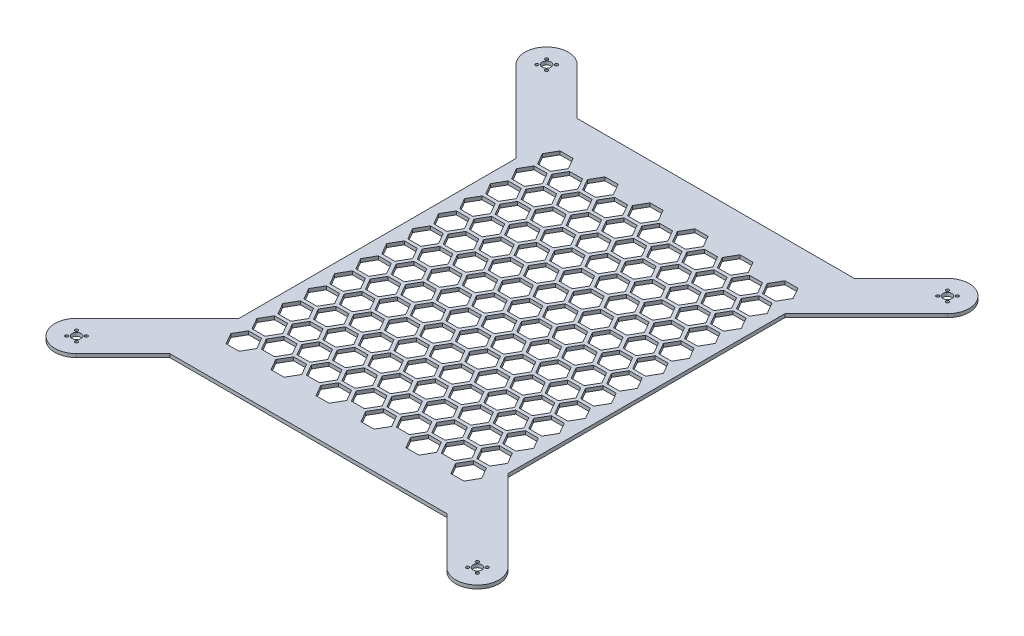
SolidWorks part; units mm, degrees
material "2014-T4"
ref_plane "Front Plane" through (0, 0, 0) normal (0, 0, 1) x (1, 0, 0)
ref_plane "Top Plane" through (0, 0, 0) normal (0, 1, 0) x (1, 0, 0)
ref_plane "Right Plane" through (0, 0, 0) normal (1, 0, 0) x (0, 0, -1)
sketch "Sketch1" plane through (0, 0, 0) normal (0, 1, 0) x (1, 0, 0)
  line L0 (-17.6777, 17.6777) -> (76.1947, 111.55)
  line L1 (17.6777, -17.6777) -> (71.55, 36.1947)
  line L2 (71.55, 36.1947) -> (391.55, 36.1947)
  line L3 (391.55, 36.1947) -> (445.4223, -17.6777)
  line L4 (480.7777, 17.6777) -> (386.9053, 111.55)
  line L5 (386.9053, 111.55) -> (386.9053, 431.55)
  line L6 (386.9053, 431.55) -> (480.7777, 525.4223)
  line L7 (445.4223, 560.7777) -> (391.55, 506.9053)
  line L8 (391.55, 506.9053) -> (71.55, 506.9053)
  line L9 (71.55, 506.9053) -> (17.6777, 560.7777)
  line L10 (-17.6777, 525.4223) -> (76.1947, 431.55)
  line L11 (76.1947, 431.55) -> (76.1947, 111.55)
  line L12 (480.7777, 17.6777) -> (463.1, 0) construction
  line L13 (463.1, 0) -> (427.7447, -35.3553) construction
  line L14 (-17.6777, 17.6777) -> (0, 0) construction
  line L15 (0, 0) -> (35.3553, -35.3553) construction
  line L16 (17.6777, 560.7777) -> (0, 543.1) construction
  line L17 (0, 543.1) -> (-35.3553, 507.7447) construction
  line L18 (445.4223, 560.7777) -> (463.1, 543.1) construction
  line L19 (463.1, 543.1) -> (498.4553, 507.7447) construction
  arc A0 (-17.6777, 17.6777) -> (17.6777, -17.6777) centre (0, 0) ccw
  arc A1 (445.4223, -17.6777) -> (480.7777, 17.6777) centre (463.1, 0) ccw
  arc A2 (480.7777, 525.4223) -> (445.4223, 560.7777) centre (463.1, 543.1) ccw
  arc A3 (17.6777, 560.7777) -> (-17.6777, 525.4223) centre (0, 543.1) ccw
  dimension "D1" = 25
  dimension "D2" = 25
  dimension "D3" = 25
  dimension "D4" = 25
  dimension "D5" = 463.1
  dimension "D6" = 543.1
  dimension "D7" = 320
  dimension "D8" = 320
  dimension "D9" = 135
extrude "Boss-Extrude1" add sketch "Sketch1" along normal blind 4
sketch "Sketch2" plane through (0, 4, 0) normal (0, 1, 0) x (1, 0, 0)
sketch "Sketch4" plane through (0, 4, 0) normal (0, 1, 0) x (1, 0, 0)
  line L0 (135.1254, 423.5646) -> (142.6254, 436.555)
  line L1 (109.1447, 438.5646) -> (116.6447, 451.555)
  line L2 (116.6447, 451.555) -> (109.1447, 464.5453)
  line L3 (109.1447, 464.5453) -> (94.1447, 464.5453)
  line L4 (94.1447, 464.5453) -> (86.6447, 451.555)
  line L5 (86.6447, 451.555) -> (94.1447, 438.5646)
  line L6 (94.1447, 438.5646) -> (109.1447, 438.5646)
  line L7 (142.6254, 436.555) -> (135.1254, 449.5453)
  line L8 (135.1254, 449.5453) -> (120.1254, 449.5453)
  line L9 (120.1254, 449.5453) -> (112.6254, 436.555)
  line L10 (112.6254, 436.555) -> (120.1254, 423.5646)
  line L11 (120.1254, 423.5646) -> (135.1254, 423.5646)
  line L12 (161.1062, 408.5646) -> (168.6062, 421.555)
  line L13 (168.6062, 421.555) -> (161.1062, 434.5453)
  line L14 (161.1062, 434.5453) -> (146.1062, 434.5453)
  line L15 (146.1062, 434.5453) -> (138.6062, 421.555)
  line L16 (138.6062, 421.555) -> (146.1062, 408.5646)
  line L17 (146.1062, 408.5646) -> (161.1062, 408.5646)
  line L18 (187.0869, 393.5646) -> (194.5869, 406.555)
  line L19 (194.5869, 406.555) -> (187.0869, 419.5453)
  line L20 (187.0869, 419.5453) -> (172.0869, 419.5453)
  line L21 (172.0869, 419.5453) -> (164.5869, 406.555)
  line L22 (164.5869, 406.555) -> (172.0869, 393.5646)
  line L23 (172.0869, 393.5646) -> (187.0869, 393.5646)
  line L24 (213.0677, 378.5646) -> (220.5677, 391.555)
  line L25 (220.5677, 391.555) -> (213.0677, 404.5453)
  line L26 (213.0677, 404.5453) -> (198.0677, 404.5453)
  line L27 (198.0677, 404.5453) -> (190.5677, 391.555)
  line L28 (190.5677, 391.555) -> (198.0677, 378.5646)
  line L29 (198.0677, 378.5646) -> (213.0677, 378.5646)
  line L30 (239.0485, 363.5646) -> (246.5485, 376.555)
  line L31 (246.5485, 376.555) -> (239.0485, 389.5453)
  line L32 (239.0485, 389.5453) -> (224.0485, 389.5453)
  line L33 (224.0485, 389.5453) -> (216.5485, 376.555)
  line L34 (216.5485, 376.555) -> (224.0485, 363.5646)
  line L35 (224.0485, 363.5646) -> (239.0485, 363.5646)
  line L36 (265.0292, 348.5646) -> (272.5292, 361.555)
  line L37 (272.5292, 361.555) -> (265.0292, 374.5453)
  line L38 (265.0292, 374.5453) -> (250.0292, 374.5453)
  line L39 (250.0292, 374.5453) -> (242.5292, 361.555)
  line L40 (242.5292, 361.555) -> (250.0292, 348.5646)
  line L41 (250.0292, 348.5646) -> (265.0292, 348.5646)
  line L42 (291.01, 333.5646) -> (298.51, 346.555)
  line L43 (298.51, 346.555) -> (291.01, 359.5453)
  line L44 (291.01, 359.5453) -> (276.01, 359.5453)
  line L45 (276.01, 359.5453) -> (268.51, 346.555)
  line L46 (268.51, 346.555) -> (276.01, 333.5646)
  line L47 (276.01, 333.5646) -> (291.01, 333.5646)
  line L48 (316.9908, 318.5646) -> (324.4908, 331.555)
  line L49 (324.4908, 331.555) -> (316.9908, 344.5453)
  line L50 (316.9908, 344.5453) -> (301.9908, 344.5453)
  line L51 (301.9908, 344.5453) -> (294.4908, 331.555)
  line L52 (294.4908, 331.555) -> (301.9908, 318.5646)
  line L53 (301.9908, 318.5646) -> (316.9908, 318.5646)
  line L54 (342.9715, 303.5646) -> (350.4715, 316.555)
  line L55 (350.4715, 316.555) -> (342.9715, 329.5453)
  line L56 (342.9715, 329.5453) -> (327.9715, 329.5453)
  line L57 (327.9715, 329.5453) -> (320.4715, 316.555)
  line L58 (320.4715, 316.555) -> (327.9715, 303.5646)
  line L59 (327.9715, 303.5646) -> (342.9715, 303.5646)
  line L60 (368.9523, 288.5646) -> (376.4523, 301.555)
  line L61 (376.4523, 301.555) -> (368.9523, 314.5453)
  line L62 (368.9523, 314.5453) -> (353.9523, 314.5453)
  line L63 (353.9523, 314.5453) -> (346.4523, 301.555)
  line L64 (346.4523, 301.555) -> (353.9523, 288.5646)
  line L65 (353.9523, 288.5646) -> (368.9523, 288.5646)
  line L72 (135.1254, 393.5646) -> (142.6254, 406.555)
  line L73 (142.6254, 406.555) -> (135.1254, 419.5453)
  line L74 (135.1254, 419.5453) -> (120.1254, 419.5453)
  line L75 (120.1254, 419.5453) -> (112.6254, 406.555)
  line L76 (112.6254, 406.555) -> (120.1254, 393.5646)
  line L77 (120.1254, 393.5646) -> (135.1254, 393.5646)
  line L78 (161.1062, 378.5646) -> (168.6062, 391.555)
  line L79 (168.6062, 391.555) -> (161.1062, 404.5453)
  line L80 (161.1062, 404.5453) -> (146.1062, 404.5453)
  line L81 (146.1062, 404.5453) -> (138.6062, 391.555)
  line L82 (138.6062, 391.555) -> (146.1062, 378.5646)
  line L83 (146.1062, 378.5646) -> (161.1062, 378.5646)
  line L84 (187.0869, 363.5646) -> (194.5869, 376.555)
  line L85 (194.5869, 376.555) -> (187.0869, 389.5453)
  line L86 (187.0869, 389.5453) -> (172.0869, 389.5453)
  line L87 (172.0869, 389.5453) -> (164.5869, 376.555)
  line L88 (164.5869, 376.555) -> (172.0869, 363.5646)
  line L89 (172.0869, 363.5646) -> (187.0869, 363.5646)
  line L90 (213.0677, 348.5646) -> (220.5677, 361.555)
  line L91 (220.5677, 361.555) -> (213.0677, 374.5453)
  line L92 (213.0677, 374.5453) -> (198.0677, 374.5453)
  line L93 (198.0677, 374.5453) -> (190.5677, 361.555)
  line L94 (190.5677, 361.555) -> (198.0677, 348.5646)
  line L95 (198.0677, 348.5646) -> (213.0677, 348.5646)
  line L96 (239.0485, 333.5646) -> (246.5485, 346.555)
  line L97 (246.5485, 346.555) -> (239.0485, 359.5453)
  line L98 (239.0485, 359.5453) -> (224.0485, 359.5453)
  line L99 (224.0485, 359.5453) -> (216.5485, 346.555)
  line L100 (216.5485, 346.555) -> (224.0485, 333.5646)
  line L101 (224.0485, 333.5646) -> (239.0485, 333.5646)
  line L102 (265.0292, 318.5646) -> (272.5292, 331.555)
  line L103 (272.5292, 331.555) -> (265.0292, 344.5453)
  line L104 (265.0292, 344.5453) -> (250.0292, 344.5453)
  line L105 (250.0292, 344.5453) -> (242.5292, 331.555)
  line L106 (242.5292, 331.555) -> (250.0292, 318.5646)
  line L107 (250.0292, 318.5646) -> (265.0292, 318.5646)
  line L108 (291.01, 303.5646) -> (298.51, 316.555)
  line L109 (298.51, 316.555) -> (291.01, 329.5453)
  line L110 (291.01, 329.5453) -> (276.01, 329.5453)
  line L111 (276.01, 329.5453) -> (268.51, 316.555)
  line L112 (268.51, 316.555) -> (276.01, 303.5646)
  line L113 (276.01, 303.5646) -> (291.01, 303.5646)
  line L114 (316.9908, 288.5646) -> (324.4908, 301.555)
  line L115 (324.4908, 301.555) -> (316.9908, 314.5453)
  line L116 (316.9908, 314.5453) -> (301.9908, 314.5453)
  line L117 (301.9908, 314.5453) -> (294.4908, 301.555)
  line L118 (294.4908, 301.555) -> (301.9908, 288.5646)
  line L119 (301.9908, 288.5646) -> (316.9908, 288.5646)
  line L120 (342.9715, 273.5646) -> (350.4715, 286.555)
  line L121 (350.4715, 286.555) -> (342.9715, 299.5453)
  line L122 (342.9715, 299.5453) -> (327.9715, 299.5453)
  line L123 (327.9715, 299.5453) -> (320.4715, 286.555)
  line L124 (320.4715, 286.555) -> (327.9715, 273.5646)
  line L125 (327.9715, 273.5646) -> (342.9715, 273.5646)
  line L126 (368.9523, 258.5646) -> (376.4523, 271.555)
  line L127 (376.4523, 271.555) -> (368.9523, 284.5453)
  line L128 (368.9523, 284.5453) -> (353.9523, 284.5453)
  line L129 (353.9523, 284.5453) -> (346.4523, 271.555)
  line L130 (346.4523, 271.555) -> (353.9523, 258.5646)
  line L131 (353.9523, 258.5646) -> (368.9523, 258.5646)
  line L138 (135.1254, 363.5646) -> (142.6254, 376.555)
  line L139 (142.6254, 376.555) -> (135.1254, 389.5453)
  line L140 (135.1254, 389.5453) -> (120.1254, 389.5453)
  line L141 (120.1254, 389.5453) -> (112.6254, 376.555)
  line L142 (112.6254, 376.555) -> (120.1254, 363.5646)
  line L143 (120.1254, 363.5646) -> (135.1254, 363.5646)
  line L144 (161.1062, 348.5646) -> (168.6062, 361.555)
  line L145 (168.6062, 361.555) -> (161.1062, 374.5453)
  line L146 (161.1062, 374.5453) -> (146.1062, 374.5453)
  line L147 (146.1062, 374.5453) -> (138.6062, 361.555)
  line L148 (138.6062, 361.555) -> (146.1062, 348.5646)
  line L149 (146.1062, 348.5646) -> (161.1062, 348.5646)
  line L150 (187.0869, 333.5646) -> (194.5869, 346.555)
  line L151 (194.5869, 346.555) -> (187.0869, 359.5453)
  line L152 (187.0869, 359.5453) -> (172.0869, 359.5453)
  line L153 (172.0869, 359.5453) -> (164.5869, 346.555)
  line L154 (164.5869, 346.555) -> (172.0869, 333.5646)
  line L155 (172.0869, 333.5646) -> (187.0869, 333.5646)
  line L156 (213.0677, 318.5646) -> (220.5677, 331.555)
  line L157 (220.5677, 331.555) -> (213.0677, 344.5453)
  line L158 (213.0677, 344.5453) -> (198.0677, 344.5453)
  line L159 (198.0677, 344.5453) -> (190.5677, 331.555)
  line L160 (190.5677, 331.555) -> (198.0677, 318.5646)
  line L161 (198.0677, 318.5646) -> (213.0677, 318.5646)
  line L162 (239.0485, 303.5646) -> (246.5485, 316.555)
  line L163 (246.5485, 316.555) -> (239.0485, 329.5453)
  line L164 (239.0485, 329.5453) -> (224.0485, 329.5453)
  line L165 (224.0485, 329.5453) -> (216.5485, 316.555)
  line L166 (216.5485, 316.555) -> (224.0485, 303.5646)
  line L167 (224.0485, 303.5646) -> (239.0485, 303.5646)
  line L168 (265.0292, 288.5646) -> (272.5292, 301.555)
  line L169 (272.5292, 301.555) -> (265.0292, 314.5453)
  line L170 (265.0292, 314.5453) -> (250.0292, 314.5453)
  line L171 (250.0292, 314.5453) -> (242.5292, 301.555)
  line L172 (242.5292, 301.555) -> (250.0292, 288.5646)
  line L173 (250.0292, 288.5646) -> (265.0292, 288.5646)
  line L174 (291.01, 273.5646) -> (298.51, 286.555)
  line L175 (298.51, 286.555) -> (291.01, 299.5453)
  line L176 (291.01, 299.5453) -> (276.01, 299.5453)
  line L177 (276.01, 299.5453) -> (268.51, 286.555)
  line L178 (268.51, 286.555) -> (276.01, 273.5646)
  line L179 (276.01, 273.5646) -> (291.01, 273.5646)
  line L180 (316.9908, 258.5646) -> (324.4908, 271.555)
  line L181 (324.4908, 271.555) -> (316.9908, 284.5453)
  line L182 (316.9908, 284.5453) -> (301.9908, 284.5453)
  line L183 (301.9908, 284.5453) -> (294.4908, 271.555)
  line L184 (294.4908, 271.555) -> (301.9908, 258.5646)
  line L185 (301.9908, 258.5646) -> (316.9908, 258.5646)
  line L186 (342.9715, 243.5646) -> (350.4715, 256.555)
  line L187 (350.4715, 256.555) -> (342.9715, 269.5453)
  line L188 (342.9715, 269.5453) -> (327.9715, 269.5453)
  line L189 (327.9715, 269.5453) -> (320.4715, 256.555)
  line L190 (320.4715, 256.555) -> (327.9715, 243.5646)
  line L191 (327.9715, 243.5646) -> (342.9715, 243.5646)
  line L192 (368.9523, 228.5646) -> (376.4523, 241.555)
  line L193 (376.4523, 241.555) -> (368.9523, 254.5453)
  line L194 (368.9523, 254.5453) -> (353.9523, 254.5453)
  line L195 (353.9523, 254.5453) -> (346.4523, 241.555)
  line L196 (346.4523, 241.555) -> (353.9523, 228.5646)
  line L197 (353.9523, 228.5646) -> (368.9523, 228.5646)
  line L204 (135.1254, 333.5646) -> (142.6254, 346.555)
  line L205 (142.6254, 346.555) -> (135.1254, 359.5453)
  line L206 (135.1254, 359.5453) -> (120.1254, 359.5453)
  line L207 (120.1254, 359.5453) -> (112.6254, 346.555)
  line L208 (112.6254, 346.555) -> (120.1254, 333.5646)
  line L209 (120.1254, 333.5646) -> (135.1254, 333.5646)
  line L210 (161.1062, 318.5646) -> (168.6062, 331.555)
  line L211 (168.6062, 331.555) -> (161.1062, 344.5453)
  line L212 (161.1062, 344.5453) -> (146.1062, 344.5453)
  line L213 (146.1062, 344.5453) -> (138.6062, 331.555)
  line L214 (138.6062, 331.555) -> (146.1062, 318.5646)
  line L215 (146.1062, 318.5646) -> (161.1062, 318.5646)
  line L216 (187.0869, 303.5646) -> (194.5869, 316.555)
  line L217 (194.5869, 316.555) -> (187.0869, 329.5453)
  line L218 (187.0869, 329.5453) -> (172.0869, 329.5453)
  line L219 (172.0869, 329.5453) -> (164.5869, 316.555)
  line L220 (164.5869, 316.555) -> (172.0869, 303.5646)
  line L221 (172.0869, 303.5646) -> (187.0869, 303.5646)
  line L222 (213.0677, 288.5646) -> (220.5677, 301.555)
  line L223 (220.5677, 301.555) -> (213.0677, 314.5453)
  line L224 (213.0677, 314.5453) -> (198.0677, 314.5453)
  line L225 (198.0677, 314.5453) -> (190.5677, 301.555)
  line L226 (190.5677, 301.555) -> (198.0677, 288.5646)
  line L227 (198.0677, 288.5646) -> (213.0677, 288.5646)
  line L228 (239.0485, 273.5646) -> (246.5485, 286.555)
  line L229 (246.5485, 286.555) -> (239.0485, 299.5453)
  line L230 (239.0485, 299.5453) -> (224.0485, 299.5453)
  line L231 (224.0485, 299.5453) -> (216.5485, 286.555)
  line L232 (216.5485, 286.555) -> (224.0485, 273.5646)
  line L233 (224.0485, 273.5646) -> (239.0485, 273.5646)
  line L234 (265.0292, 258.5646) -> (272.5292, 271.555)
  line L235 (272.5292, 271.555) -> (265.0292, 284.5453)
  line L236 (265.0292, 284.5453) -> (250.0292, 284.5453)
  line L237 (250.0292, 284.5453) -> (242.5292, 271.555)
  line L238 (242.5292, 271.555) -> (250.0292, 258.5646)
  line L239 (250.0292, 258.5646) -> (265.0292, 258.5646)
  line L240 (291.01, 243.5646) -> (298.51, 256.555)
  line L241 (298.51, 256.555) -> (291.01, 269.5453)
  line L242 (291.01, 269.5453) -> (276.01, 269.5453)
  line L243 (276.01, 269.5453) -> (268.51, 256.555)
  line L244 (268.51, 256.555) -> (276.01, 243.5646)
  line L245 (276.01, 243.5646) -> (291.01, 243.5646)
  line L246 (316.9908, 228.5646) -> (324.4908, 241.555)
  line L247 (324.4908, 241.555) -> (316.9908, 254.5453)
  line L248 (316.9908, 254.5453) -> (301.9908, 254.5453)
  line L249 (301.9908, 254.5453) -> (294.4908, 241.555)
  line L250 (294.4908, 241.555) -> (301.9908, 228.5646)
  line L251 (301.9908, 228.5646) -> (316.9908, 228.5646)
  line L252 (342.9715, 213.5646) -> (350.4715, 226.555)
  line L253 (350.4715, 226.555) -> (342.9715, 239.5453)
  line L254 (342.9715, 239.5453) -> (327.9715, 239.5453)
  line L255 (327.9715, 239.5453) -> (320.4715, 226.555)
  line L256 (320.4715, 226.555) -> (327.9715, 213.5646)
  line L257 (327.9715, 213.5646) -> (342.9715, 213.5646)
  line L258 (368.9523, 198.5646) -> (376.4523, 211.555)
  line L259 (376.4523, 211.555) -> (368.9523, 224.5453)
  line L260 (368.9523, 224.5453) -> (353.9523, 224.5453)
  line L261 (353.9523, 224.5453) -> (346.4523, 211.555)
  line L262 (346.4523, 211.555) -> (353.9523, 198.5646)
  line L263 (353.9523, 198.5646) -> (368.9523, 198.5646)
  line L270 (135.1254, 303.5646) -> (142.6254, 316.555)
  line L271 (142.6254, 316.555) -> (135.1254, 329.5453)
  line L272 (135.1254, 329.5453) -> (120.1254, 329.5453)
  line L273 (120.1254, 329.5453) -> (112.6254, 316.555)
  line L274 (112.6254, 316.555) -> (120.1254, 303.5646)
  line L275 (120.1254, 303.5646) -> (135.1254, 303.5646)
  line L276 (161.1062, 288.5646) -> (168.6062, 301.555)
  line L277 (168.6062, 301.555) -> (161.1062, 314.5453)
  line L278 (161.1062, 314.5453) -> (146.1062, 314.5453)
  line L279 (146.1062, 314.5453) -> (138.6062, 301.555)
  line L280 (138.6062, 301.555) -> (146.1062, 288.5646)
  line L281 (146.1062, 288.5646) -> (161.1062, 288.5646)
  line L282 (187.0869, 273.5646) -> (194.5869, 286.555)
  line L283 (194.5869, 286.555) -> (187.0869, 299.5453)
  line L284 (187.0869, 299.5453) -> (172.0869, 299.5453)
  line L285 (172.0869, 299.5453) -> (164.5869, 286.555)
  line L286 (164.5869, 286.555) -> (172.0869, 273.5646)
  line L287 (172.0869, 273.5646) -> (187.0869, 273.5646)
  line L288 (213.0677, 258.5646) -> (220.5677, 271.555)
  line L289 (220.5677, 271.555) -> (213.0677, 284.5453)
  line L290 (213.0677, 284.5453) -> (198.0677, 284.5453)
  line L291 (198.0677, 284.5453) -> (190.5677, 271.555)
  line L292 (190.5677, 271.555) -> (198.0677, 258.5646)
  line L293 (198.0677, 258.5646) -> (213.0677, 258.5646)
  line L294 (239.0485, 243.5646) -> (246.5485, 256.555)
  line L295 (246.5485, 256.555) -> (239.0485, 269.5453)
  line L296 (239.0485, 269.5453) -> (224.0485, 269.5453)
  line L297 (224.0485, 269.5453) -> (216.5485, 256.555)
  line L298 (216.5485, 256.555) -> (224.0485, 243.5646)
  line L299 (224.0485, 243.5646) -> (239.0485, 243.5646)
  line L300 (265.0292, 228.5646) -> (272.5292, 241.555)
  line L301 (272.5292, 241.555) -> (265.0292, 254.5453)
  line L302 (265.0292, 254.5453) -> (250.0292, 254.5453)
  line L303 (250.0292, 254.5453) -> (242.5292, 241.555)
  line L304 (242.5292, 241.555) -> (250.0292, 228.5646)
  line L305 (250.0292, 228.5646) -> (265.0292, 228.5646)
  line L306 (291.01, 213.5646) -> (298.51, 226.555)
  line L307 (298.51, 226.555) -> (291.01, 239.5453)
  line L308 (291.01, 239.5453) -> (276.01, 239.5453)
  line L309 (276.01, 239.5453) -> (268.51, 226.555)
  line L310 (268.51, 226.555) -> (276.01, 213.5646)
  line L311 (276.01, 213.5646) -> (291.01, 213.5646)
  line L312 (316.9908, 198.5646) -> (324.4908, 211.555)
  line L313 (324.4908, 211.555) -> (316.9908, 224.5453)
  line L314 (316.9908, 224.5453) -> (301.9908, 224.5453)
  line L315 (301.9908, 224.5453) -> (294.4908, 211.555)
  line L316 (294.4908, 211.555) -> (301.9908, 198.5646)
  line L317 (301.9908, 198.5646) -> (316.9908, 198.5646)
  line L318 (342.9715, 183.5646) -> (350.4715, 196.555)
  line L319 (350.4715, 196.555) -> (342.9715, 209.5453)
  line L320 (342.9715, 209.5453) -> (327.9715, 209.5453)
  line L321 (327.9715, 209.5453) -> (320.4715, 196.555)
  line L322 (320.4715, 196.555) -> (327.9715, 183.5646)
  line L323 (327.9715, 183.5646) -> (342.9715, 183.5646)
  line L324 (368.9523, 168.5646) -> (376.4523, 181.555)
  line L325 (376.4523, 181.555) -> (368.9523, 194.5453)
  line L326 (368.9523, 194.5453) -> (353.9523, 194.5453)
  line L327 (353.9523, 194.5453) -> (346.4523, 181.555)
  line L328 (346.4523, 181.555) -> (353.9523, 168.5646)
  line L329 (353.9523, 168.5646) -> (368.9523, 168.5646)
  line L336 (135.1254, 273.5646) -> (142.6254, 286.555)
  line L337 (142.6254, 286.555) -> (135.1254, 299.5453)
  line L338 (135.1254, 299.5453) -> (120.1254, 299.5453)
  line L339 (120.1254, 299.5453) -> (112.6254, 286.555)
  line L340 (112.6254, 286.555) -> (120.1254, 273.5646)
  line L341 (120.1254, 273.5646) -> (135.1254, 273.5646)
  line L342 (161.1062, 258.5646) -> (168.6062, 271.555)
  line L343 (168.6062, 271.555) -> (161.1062, 284.5453)
  line L344 (161.1062, 284.5453) -> (146.1062, 284.5453)
  line L345 (146.1062, 284.5453) -> (138.6062, 271.555)
  line L346 (138.6062, 271.555) -> (146.1062, 258.5646)
  line L347 (146.1062, 258.5646) -> (161.1062, 258.5646)
  line L348 (187.0869, 243.5646) -> (194.5869, 256.555)
  line L349 (194.5869, 256.555) -> (187.0869, 269.5453)
  line L350 (187.0869, 269.5453) -> (172.0869, 269.5453)
  line L351 (172.0869, 269.5453) -> (164.5869, 256.555)
  line L352 (164.5869, 256.555) -> (172.0869, 243.5646)
  line L353 (172.0869, 243.5646) -> (187.0869, 243.5646)
  line L354 (213.0677, 228.5646) -> (220.5677, 241.555)
  line L355 (220.5677, 241.555) -> (213.0677, 254.5453)
  line L356 (213.0677, 254.5453) -> (198.0677, 254.5453)
  line L357 (198.0677, 254.5453) -> (190.5677, 241.555)
  line L358 (190.5677, 241.555) -> (198.0677, 228.5646)
  line L359 (198.0677, 228.5646) -> (213.0677, 228.5646)
  line L360 (239.0485, 213.5646) -> (246.5485, 226.555)
  line L361 (246.5485, 226.555) -> (239.0485, 239.5453)
  line L362 (239.0485, 239.5453) -> (224.0485, 239.5453)
  line L363 (224.0485, 239.5453) -> (216.5485, 226.555)
  line L364 (216.5485, 226.555) -> (224.0485, 213.5646)
  line L365 (224.0485, 213.5646) -> (239.0485, 213.5646)
  line L366 (265.0292, 198.5646) -> (272.5292, 211.555)
  line L367 (272.5292, 211.555) -> (265.0292, 224.5453)
  line L368 (265.0292, 224.5453) -> (250.0292, 224.5453)
  line L369 (250.0292, 224.5453) -> (242.5292, 211.555)
  line L370 (242.5292, 211.555) -> (250.0292, 198.5646)
  line L371 (250.0292, 198.5646) -> (265.0292, 198.5646)
  line L372 (291.01, 183.5646) -> (298.51, 196.555)
  line L373 (298.51, 196.555) -> (291.01, 209.5453)
  line L374 (291.01, 209.5453) -> (276.01, 209.5453)
  line L375 (276.01, 209.5453) -> (268.51, 196.555)
  line L376 (268.51, 196.555) -> (276.01, 183.5646)
  line L377 (276.01, 183.5646) -> (291.01, 183.5646)
  line L378 (316.9908, 168.5646) -> (324.4908, 181.555)
  line L379 (324.4908, 181.555) -> (316.9908, 194.5453)
  line L380 (316.9908, 194.5453) -> (301.9908, 194.5453)
  line L381 (301.9908, 194.5453) -> (294.4908, 181.555)
  line L382 (294.4908, 181.555) -> (301.9908, 168.5646)
  line L383 (301.9908, 168.5646) -> (316.9908, 168.5646)
  line L384 (342.9715, 153.5646) -> (350.4715, 166.555)
  line L385 (350.4715, 166.555) -> (342.9715, 179.5453)
  line L386 (342.9715, 179.5453) -> (327.9715, 179.5453)
  line L387 (327.9715, 179.5453) -> (320.4715, 166.555)
  line L388 (320.4715, 166.555) -> (327.9715, 153.5646)
  line L389 (327.9715, 153.5646) -> (342.9715, 153.5646)
  line L390 (368.9523, 138.5646) -> (376.4523, 151.555)
  line L391 (376.4523, 151.555) -> (368.9523, 164.5453)
  line L392 (368.9523, 164.5453) -> (353.9523, 164.5453)
  line L393 (353.9523, 164.5453) -> (346.4523, 151.555)
  line L394 (346.4523, 151.555) -> (353.9523, 138.5646)
  line L395 (353.9523, 138.5646) -> (368.9523, 138.5646)
  line L402 (135.1254, 243.5646) -> (142.6254, 256.555)
  line L403 (142.6254, 256.555) -> (135.1254, 269.5453)
  line L404 (135.1254, 269.5453) -> (120.1254, 269.5453)
  line L405 (120.1254, 269.5453) -> (112.6254, 256.555)
  line L406 (112.6254, 256.555) -> (120.1254, 243.5646)
  line L407 (120.1254, 243.5646) -> (135.1254, 243.5646)
  line L408 (161.1062, 228.5646) -> (168.6062, 241.555)
  line L409 (168.6062, 241.555) -> (161.1062, 254.5453)
  line L410 (161.1062, 254.5453) -> (146.1062, 254.5453)
  line L411 (146.1062, 254.5453) -> (138.6062, 241.555)
  line L412 (138.6062, 241.555) -> (146.1062, 228.5646)
  line L413 (146.1062, 228.5646) -> (161.1062, 228.5646)
  line L414 (187.0869, 213.5646) -> (194.5869, 226.555)
  line L415 (194.5869, 226.555) -> (187.0869, 239.5453)
  line L416 (187.0869, 239.5453) -> (172.0869, 239.5453)
  line L417 (172.0869, 239.5453) -> (164.5869, 226.555)
  line L418 (164.5869, 226.555) -> (172.0869, 213.5646)
  line L419 (172.0869, 213.5646) -> (187.0869, 213.5646)
  line L420 (213.0677, 198.5646) -> (220.5677, 211.555)
  line L421 (220.5677, 211.555) -> (213.0677, 224.5453)
  line L422 (213.0677, 224.5453) -> (198.0677, 224.5453)
  line L423 (198.0677, 224.5453) -> (190.5677, 211.555)
  line L424 (190.5677, 211.555) -> (198.0677, 198.5646)
  line L425 (198.0677, 198.5646) -> (213.0677, 198.5646)
  line L426 (239.0485, 183.5646) -> (246.5485, 196.555)
  line L427 (246.5485, 196.555) -> (239.0485, 209.5453)
  line L428 (239.0485, 209.5453) -> (224.0485, 209.5453)
  line L429 (224.0485, 209.5453) -> (216.5485, 196.555)
  line L430 (216.5485, 196.555) -> (224.0485, 183.5646)
  line L431 (224.0485, 183.5646) -> (239.0485, 183.5646)
  line L432 (265.0292, 168.5646) -> (272.5292, 181.555)
  line L433 (272.5292, 181.555) -> (265.0292, 194.5453)
  line L434 (265.0292, 194.5453) -> (250.0292, 194.5453)
  line L435 (250.0292, 194.5453) -> (242.5292, 181.555)
  line L436 (242.5292, 181.555) -> (250.0292, 168.5646)
  line L437 (250.0292, 168.5646) -> (265.0292, 168.5646)
  line L438 (291.01, 153.5646) -> (298.51, 166.555)
  line L439 (298.51, 166.555) -> (291.01, 179.5453)
  line L440 (291.01, 179.5453) -> (276.01, 179.5453)
  line L441 (276.01, 179.5453) -> (268.51, 166.555)
  line L442 (268.51, 166.555) -> (276.01, 153.5646)
  line L443 (276.01, 153.5646) -> (291.01, 153.5646)
  line L444 (316.9908, 138.5646) -> (324.4908, 151.555)
  line L445 (324.4908, 151.555) -> (316.9908, 164.5453)
  line L446 (316.9908, 164.5453) -> (301.9908, 164.5453)
  line L447 (301.9908, 164.5453) -> (294.4908, 151.555)
  line L448 (294.4908, 151.555) -> (301.9908, 138.5646)
  line L449 (301.9908, 138.5646) -> (316.9908, 138.5646)
  line L450 (342.9715, 123.5646) -> (350.4715, 136.555)
  line L451 (350.4715, 136.555) -> (342.9715, 149.5453)
  line L452 (342.9715, 149.5453) -> (327.9715, 149.5453)
  line L453 (327.9715, 149.5453) -> (320.4715, 136.555)
  line L454 (320.4715, 136.555) -> (327.9715, 123.5646)
  line L455 (327.9715, 123.5646) -> (342.9715, 123.5646)
  line L456 (368.9523, 108.5646) -> (376.4523, 121.555)
  line L457 (376.4523, 121.555) -> (368.9523, 134.5453)
  line L458 (368.9523, 134.5453) -> (353.9523, 134.5453)
  line L459 (353.9523, 134.5453) -> (346.4523, 121.555)
  line L460 (346.4523, 121.555) -> (353.9523, 108.5646)
  line L461 (353.9523, 108.5646) -> (368.9523, 108.5646)
  line L468 (135.1254, 213.5646) -> (142.6254, 226.555)
  line L469 (142.6254, 226.555) -> (135.1254, 239.5453)
  line L470 (135.1254, 239.5453) -> (120.1254, 239.5453)
  line L471 (120.1254, 239.5453) -> (112.6254, 226.555)
  line L472 (112.6254, 226.555) -> (120.1254, 213.5646)
  line L473 (120.1254, 213.5646) -> (135.1254, 213.5646)
  line L474 (161.1062, 198.5646) -> (168.6062, 211.555)
  line L475 (168.6062, 211.555) -> (161.1062, 224.5453)
  line L476 (161.1062, 224.5453) -> (146.1062, 224.5453)
  line L477 (146.1062, 224.5453) -> (138.6062, 211.555)
  line L478 (138.6062, 211.555) -> (146.1062, 198.5646)
  line L479 (146.1062, 198.5646) -> (161.1062, 198.5646)
  line L480 (187.0869, 183.5646) -> (194.5869, 196.555)
  line L481 (194.5869, 196.555) -> (187.0869, 209.5453)
  line L482 (187.0869, 209.5453) -> (172.0869, 209.5453)
  line L483 (172.0869, 209.5453) -> (164.5869, 196.555)
  line L484 (164.5869, 196.555) -> (172.0869, 183.5646)
  line L485 (172.0869, 183.5646) -> (187.0869, 183.5646)
  line L486 (213.0677, 168.5646) -> (220.5677, 181.555)
  line L487 (220.5677, 181.555) -> (213.0677, 194.5453)
  line L488 (213.0677, 194.5453) -> (198.0677, 194.5453)
  line L489 (198.0677, 194.5453) -> (190.5677, 181.555)
  line L490 (190.5677, 181.555) -> (198.0677, 168.5646)
  line L491 (198.0677, 168.5646) -> (213.0677, 168.5646)
  line L492 (239.0485, 153.5646) -> (246.5485, 166.555)
  line L493 (246.5485, 166.555) -> (239.0485, 179.5453)
  line L494 (239.0485, 179.5453) -> (224.0485, 179.5453)
  line L495 (224.0485, 179.5453) -> (216.5485, 166.555)
  line L496 (216.5485, 166.555) -> (224.0485, 153.5646)
  line L497 (224.0485, 153.5646) -> (239.0485, 153.5646)
  line L498 (265.0292, 138.5646) -> (272.5292, 151.555)
  line L499 (272.5292, 151.555) -> (265.0292, 164.5453)
  line L500 (265.0292, 164.5453) -> (250.0292, 164.5453)
  line L501 (250.0292, 164.5453) -> (242.5292, 151.555)
  line L502 (242.5292, 151.555) -> (250.0292, 138.5646)
  line L503 (250.0292, 138.5646) -> (265.0292, 138.5646)
  line L504 (291.01, 123.5646) -> (298.51, 136.555)
  line L505 (298.51, 136.555) -> (291.01, 149.5453)
  line L506 (291.01, 149.5453) -> (276.01, 149.5453)
  line L507 (276.01, 149.5453) -> (268.51, 136.555)
  line L508 (268.51, 136.555) -> (276.01, 123.5646)
  line L509 (276.01, 123.5646) -> (291.01, 123.5646)
  line L510 (316.9908, 108.5646) -> (324.4908, 121.555)
  line L511 (324.4908, 121.555) -> (316.9908, 134.5453)
  line L512 (316.9908, 134.5453) -> (301.9908, 134.5453)
  line L513 (301.9908, 134.5453) -> (294.4908, 121.555)
  line L514 (294.4908, 121.555) -> (301.9908, 108.5646)
  line L515 (301.9908, 108.5646) -> (316.9908, 108.5646)
  line L516 (342.9715, 93.5646) -> (350.4715, 106.555)
  line L517 (350.4715, 106.555) -> (342.9715, 119.5453)
  line L518 (342.9715, 119.5453) -> (327.9715, 119.5453)
  line L519 (327.9715, 119.5453) -> (320.4715, 106.555)
  line L520 (320.4715, 106.555) -> (327.9715, 93.5646)
  line L521 (327.9715, 93.5646) -> (342.9715, 93.5646)
  line L522 (368.9523, 78.5646) -> (376.4523, 91.555)
  line L523 (376.4523, 91.555) -> (368.9523, 104.5453)
  line L524 (368.9523, 104.5453) -> (353.9523, 104.5453)
  line L525 (353.9523, 104.5453) -> (346.4523, 91.555)
  line L526 (346.4523, 91.555) -> (353.9523, 78.5646)
  line L527 (353.9523, 78.5646) -> (368.9523, 78.5646)
  line L534 (135.1254, 183.5646) -> (142.6254, 196.555)
  line L535 (142.6254, 196.555) -> (135.1254, 209.5453)
  line L536 (135.1254, 209.5453) -> (120.1254, 209.5453)
  line L537 (120.1254, 209.5453) -> (112.6254, 196.555)
  line L538 (112.6254, 196.555) -> (120.1254, 183.5646)
  line L539 (120.1254, 183.5646) -> (135.1254, 183.5646)
  line L540 (161.1062, 168.5646) -> (168.6062, 181.555)
  line L541 (168.6062, 181.555) -> (161.1062, 194.5453)
  line L542 (161.1062, 194.5453) -> (146.1062, 194.5453)
  line L543 (146.1062, 194.5453) -> (138.6062, 181.555)
  line L544 (138.6062, 181.555) -> (146.1062, 168.5646)
  line L545 (146.1062, 168.5646) -> (161.1062, 168.5646)
  line L546 (187.0869, 153.5646) -> (194.5869, 166.555)
  line L547 (194.5869, 166.555) -> (187.0869, 179.5453)
  line L548 (187.0869, 179.5453) -> (172.0869, 179.5453)
  line L549 (172.0869, 179.5453) -> (164.5869, 166.555)
  line L550 (164.5869, 166.555) -> (172.0869, 153.5646)
  line L551 (172.0869, 153.5646) -> (187.0869, 153.5646)
  line L552 (213.0677, 138.5646) -> (220.5677, 151.555)
  line L553 (220.5677, 151.555) -> (213.0677, 164.5453)
  line L554 (213.0677, 164.5453) -> (198.0677, 164.5453)
  line L555 (198.0677, 164.5453) -> (190.5677, 151.555)
  line L556 (190.5677, 151.555) -> (198.0677, 138.5646)
  line L557 (198.0677, 138.5646) -> (213.0677, 138.5646)
  line L558 (239.0485, 123.5646) -> (246.5485, 136.555)
  line L559 (246.5485, 136.555) -> (239.0485, 149.5453)
  line L560 (239.0485, 149.5453) -> (224.0485, 149.5453)
  line L561 (224.0485, 149.5453) -> (216.5485, 136.555)
  line L562 (216.5485, 136.555) -> (224.0485, 123.5646)
  line L563 (224.0485, 123.5646) -> (239.0485, 123.5646)
  line L564 (265.0292, 108.5646) -> (272.5292, 121.555)
  line L565 (272.5292, 121.555) -> (265.0292, 134.5453)
  line L566 (265.0292, 134.5453) -> (250.0292, 134.5453)
  line L567 (250.0292, 134.5453) -> (242.5292, 121.555)
  line L568 (242.5292, 121.555) -> (250.0292, 108.5646)
  line L569 (250.0292, 108.5646) -> (265.0292, 108.5646)
  line L570 (291.01, 93.5646) -> (298.51, 106.555)
  line L571 (298.51, 106.555) -> (291.01, 119.5453)
  line L572 (291.01, 119.5453) -> (276.01, 119.5453)
  line L573 (276.01, 119.5453) -> (268.51, 106.555)
  line L574 (268.51, 106.555) -> (276.01, 93.5646)
  line L575 (276.01, 93.5646) -> (291.01, 93.5646)
  line L576 (316.9908, 78.5646) -> (324.4908, 91.555)
  line L577 (324.4908, 91.555) -> (316.9908, 104.5453)
  line L578 (316.9908, 104.5453) -> (301.9908, 104.5453)
  line L579 (301.9908, 104.5453) -> (294.4908, 91.555)
  line L580 (294.4908, 91.555) -> (301.9908, 78.5646)
  line L581 (301.9908, 78.5646) -> (316.9908, 78.5646)
  line L600 (135.1254, 153.5646) -> (142.6254, 166.555)
  line L601 (142.6254, 166.555) -> (135.1254, 179.5453)
  line L602 (135.1254, 179.5453) -> (120.1254, 179.5453)
  line L603 (120.1254, 179.5453) -> (112.6254, 166.555)
  line L604 (112.6254, 166.555) -> (120.1254, 153.5646)
  line L605 (120.1254, 153.5646) -> (135.1254, 153.5646)
  line L606 (161.1062, 138.5646) -> (168.6062, 151.555)
  line L607 (168.6062, 151.555) -> (161.1062, 164.5453)
  line L608 (161.1062, 164.5453) -> (146.1062, 164.5453)
  line L609 (146.1062, 164.5453) -> (138.6062, 151.555)
  line L610 (138.6062, 151.555) -> (146.1062, 138.5646)
  line L611 (146.1062, 138.5646) -> (161.1062, 138.5646)
  line L612 (187.0869, 123.5646) -> (194.5869, 136.555)
  line L613 (194.5869, 136.555) -> (187.0869, 149.5453)
  line L614 (187.0869, 149.5453) -> (172.0869, 149.5453)
  line L615 (172.0869, 149.5453) -> (164.5869, 136.555)
  line L616 (164.5869, 136.555) -> (172.0869, 123.5646)
  line L617 (172.0869, 123.5646) -> (187.0869, 123.5646)
  line L618 (213.0677, 108.5646) -> (220.5677, 121.555)
  line L619 (220.5677, 121.555) -> (213.0677, 134.5453)
  line L620 (213.0677, 134.5453) -> (198.0677, 134.5453)
  line L621 (198.0677, 134.5453) -> (190.5677, 121.555)
  line L622 (190.5677, 121.555) -> (198.0677, 108.5646)
  line L623 (198.0677, 108.5646) -> (213.0677, 108.5646)
  line L624 (239.0485, 93.5646) -> (246.5485, 106.555)
  line L625 (246.5485, 106.555) -> (239.0485, 119.5453)
  line L626 (239.0485, 119.5453) -> (224.0485, 119.5453)
  line L627 (224.0485, 119.5453) -> (216.5485, 106.555)
  line L628 (216.5485, 106.555) -> (224.0485, 93.5646)
  line L629 (224.0485, 93.5646) -> (239.0485, 93.5646)
  line L630 (265.0292, 78.5646) -> (272.5292, 91.555)
  line L631 (272.5292, 91.555) -> (265.0292, 104.5453)
  line L632 (265.0292, 104.5453) -> (250.0292, 104.5453)
  line L633 (250.0292, 104.5453) -> (242.5292, 91.555)
  line L634 (242.5292, 91.555) -> (250.0292, 78.5646)
  line L635 (250.0292, 78.5646) -> (265.0292, 78.5646)
  line L666 (135.1254, 123.5646) -> (142.6254, 136.555)
  line L667 (142.6254, 136.555) -> (135.1254, 149.5453)
  line L668 (135.1254, 149.5453) -> (120.1254, 149.5453)
  line L669 (120.1254, 149.5453) -> (112.6254, 136.555)
  line L670 (112.6254, 136.555) -> (120.1254, 123.5646)
  line L671 (120.1254, 123.5646) -> (135.1254, 123.5646)
  line L672 (161.1062, 108.5646) -> (168.6062, 121.555)
  line L673 (168.6062, 121.555) -> (161.1062, 134.5453)
  line L674 (161.1062, 134.5453) -> (146.1062, 134.5453)
  line L675 (146.1062, 134.5453) -> (138.6062, 121.555)
  line L676 (138.6062, 121.555) -> (146.1062, 108.5646)
  line L677 (146.1062, 108.5646) -> (161.1062, 108.5646)
  line L678 (187.0869, 93.5646) -> (194.5869, 106.555)
  line L679 (194.5869, 106.555) -> (187.0869, 119.5453)
  line L680 (187.0869, 119.5453) -> (172.0869, 119.5453)
  line L681 (172.0869, 119.5453) -> (164.5869, 106.555)
  line L682 (164.5869, 106.555) -> (172.0869, 93.5646)
  line L683 (172.0869, 93.5646) -> (187.0869, 93.5646)
  line L684 (213.0677, 78.5646) -> (220.5677, 91.555)
  line L685 (220.5677, 91.555) -> (213.0677, 104.5453)
  line L686 (213.0677, 104.5453) -> (198.0677, 104.5453)
  line L687 (198.0677, 104.5453) -> (190.5677, 91.555)
  line L688 (190.5677, 91.555) -> (198.0677, 78.5646)
  line L689 (198.0677, 78.5646) -> (213.0677, 78.5646)
  line L732 (135.1254, 93.5646) -> (142.6254, 106.555)
  line L733 (142.6254, 106.555) -> (135.1254, 119.5453)
  line L734 (135.1254, 119.5453) -> (120.1254, 119.5453)
  line L735 (120.1254, 119.5453) -> (112.6254, 106.555)
  line L736 (112.6254, 106.555) -> (120.1254, 93.5646)
  line L737 (120.1254, 93.5646) -> (135.1254, 93.5646)
  line L738 (161.1062, 78.5646) -> (168.6062, 91.555)
  line L739 (168.6062, 91.555) -> (161.1062, 104.5453)
  line L740 (161.1062, 104.5453) -> (146.1062, 104.5453)
  line L741 (146.1062, 104.5453) -> (138.6062, 91.555)
  line L742 (138.6062, 91.555) -> (146.1062, 78.5646)
  line L743 (146.1062, 78.5646) -> (161.1062, 78.5646)
  line L864 (109.1447, 408.5646) -> (116.6447, 421.555)
  line L865 (116.6447, 421.555) -> (109.1447, 434.5453)
  line L866 (109.1447, 434.5453) -> (94.1447, 434.5453)
  line L867 (94.1447, 434.5453) -> (86.6447, 421.555)
  line L868 (86.6447, 421.555) -> (94.1447, 408.5646)
  line L869 (94.1447, 408.5646) -> (109.1447, 408.5646)
  line L870 (109.1447, 378.5646) -> (116.6447, 391.555)
  line L871 (116.6447, 391.555) -> (109.1447, 404.5453)
  line L872 (109.1447, 404.5453) -> (94.1447, 404.5453)
  line L873 (94.1447, 404.5453) -> (86.6447, 391.555)
  line L874 (86.6447, 391.555) -> (94.1447, 378.5646)
  line L875 (94.1447, 378.5646) -> (109.1447, 378.5646)
  line L876 (109.1447, 348.5646) -> (116.6447, 361.555)
  line L877 (116.6447, 361.555) -> (109.1447, 374.5453)
  line L878 (109.1447, 374.5453) -> (94.1447, 374.5453)
  line L879 (94.1447, 374.5453) -> (86.6447, 361.555)
  line L880 (86.6447, 361.555) -> (94.1447, 348.5646)
  line L881 (94.1447, 348.5646) -> (109.1447, 348.5646)
  line L882 (109.1447, 318.5646) -> (116.6447, 331.555)
  line L883 (116.6447, 331.555) -> (109.1447, 344.5453)
  line L884 (109.1447, 344.5453) -> (94.1447, 344.5453)
  line L885 (94.1447, 344.5453) -> (86.6447, 331.555)
  line L886 (86.6447, 331.555) -> (94.1447, 318.5646)
  line L887 (94.1447, 318.5646) -> (109.1447, 318.5646)
  line L888 (109.1447, 288.5646) -> (116.6447, 301.555)
  line L889 (116.6447, 301.555) -> (109.1447, 314.5453)
  line L890 (109.1447, 314.5453) -> (94.1447, 314.5453)
  line L891 (94.1447, 314.5453) -> (86.6447, 301.555)
  line L892 (86.6447, 301.555) -> (94.1447, 288.5646)
  line L893 (94.1447, 288.5646) -> (109.1447, 288.5646)
  line L894 (109.1447, 258.5646) -> (116.6447, 271.555)
  line L895 (116.6447, 271.555) -> (109.1447, 284.5453)
  line L896 (109.1447, 284.5453) -> (94.1447, 284.5453)
  line L897 (94.1447, 284.5453) -> (86.6447, 271.555)
  line L898 (86.6447, 271.555) -> (94.1447, 258.5646)
  line L899 (94.1447, 258.5646) -> (109.1447, 258.5646)
  line L900 (109.1447, 228.5646) -> (116.6447, 241.555)
  line L901 (116.6447, 241.555) -> (109.1447, 254.5453)
  line L902 (109.1447, 254.5453) -> (94.1447, 254.5453)
  line L903 (94.1447, 254.5453) -> (86.6447, 241.555)
  line L904 (86.6447, 241.555) -> (94.1447, 228.5646)
  line L905 (94.1447, 228.5646) -> (109.1447, 228.5646)
  line L906 (109.1447, 198.5646) -> (116.6447, 211.555)
  line L907 (116.6447, 211.555) -> (109.1447, 224.5453)
  line L908 (109.1447, 224.5453) -> (94.1447, 224.5453)
  line L909 (94.1447, 224.5453) -> (86.6447, 211.555)
  line L910 (86.6447, 211.555) -> (94.1447, 198.5646)
  line L911 (94.1447, 198.5646) -> (109.1447, 198.5646)
  line L912 (109.1447, 168.5646) -> (116.6447, 181.555)
  line L913 (116.6447, 181.555) -> (109.1447, 194.5453)
  line L914 (109.1447, 194.5453) -> (94.1447, 194.5453)
  line L915 (94.1447, 194.5453) -> (86.6447, 181.555)
  line L916 (86.6447, 181.555) -> (94.1447, 168.5646)
  line L917 (94.1447, 168.5646) -> (109.1447, 168.5646)
  line L918 (109.1447, 138.5646) -> (116.6447, 151.555)
  line L919 (116.6447, 151.555) -> (109.1447, 164.5453)
  line L920 (109.1447, 164.5453) -> (94.1447, 164.5453)
  line L921 (94.1447, 164.5453) -> (86.6447, 151.555)
  line L922 (86.6447, 151.555) -> (94.1447, 138.5646)
  line L923 (94.1447, 138.5646) -> (109.1447, 138.5646)
  line L924 (109.1447, 108.5646) -> (116.6447, 121.555)
  line L925 (116.6447, 121.555) -> (109.1447, 134.5453)
  line L926 (109.1447, 134.5453) -> (94.1447, 134.5453)
  line L927 (94.1447, 134.5453) -> (86.6447, 121.555)
  line L928 (86.6447, 121.555) -> (94.1447, 108.5646)
  line L929 (94.1447, 108.5646) -> (109.1447, 108.5646)
  line L930 (109.1447, 78.5646) -> (116.6447, 91.555)
  line L931 (116.6447, 91.555) -> (109.1447, 104.5453)
  line L932 (109.1447, 104.5453) -> (94.1447, 104.5453)
  line L933 (94.1447, 104.5453) -> (86.6447, 91.555)
  line L934 (86.6447, 91.555) -> (94.1447, 78.5646)
  line L935 (94.1447, 78.5646) -> (109.1447, 78.5646)
  line L936 (109.1447, 438.5646) -> (135.1254, 423.5646) construction
  line L937 (394.933, -86.4354) -> (402.433, -73.445) [skipped]
  line L938 (402.433, -73.445) -> (394.933, -60.4547) [skipped]
  line L939 (394.933, -60.4547) -> (379.933, -60.4547) [skipped]
  line L940 (379.933, -60.4547) -> (372.433, -73.445) [skipped]
  line L941 (372.433, -73.445) -> (379.933, -86.4354) [skipped]
  line L942 (379.933, -86.4354) -> (394.933, -86.4354) [skipped]
  line L943 (394.933, -56.4354) -> (402.433, -43.445) [skipped]
  line L944 (402.433, -43.445) -> (394.933, -30.4547) [skipped]
  line L945 (394.933, -30.4547) -> (379.933, -30.4547) [skipped]
  line L946 (379.933, -30.4547) -> (372.433, -43.445) [skipped]
  line L947 (372.433, -43.445) -> (379.933, -56.4354) [skipped]
  line L948 (379.933, -56.4354) -> (394.933, -56.4354) [skipped]
  line L949 (368.9523, -71.4354) -> (376.4523, -58.445) [skipped]
  line L950 (376.4523, -58.445) -> (368.9523, -45.4547) [skipped]
  line L951 (368.9523, -45.4547) -> (353.9523, -45.4547) [skipped]
  line L952 (353.9523, -45.4547) -> (346.4523, -58.445) [skipped]
  line L953 (346.4523, -58.445) -> (353.9523, -71.4354) [skipped]
  line L954 (353.9523, -71.4354) -> (368.9523, -71.4354) [skipped]
  line L955 (368.9523, -41.4354) -> (376.4523, -28.445) [skipped]
  line L956 (376.4523, -28.445) -> (368.9523, -15.4547) [skipped]
  line L957 (368.9523, -15.4547) -> (353.9523, -15.4547) [skipped]
  line L958 (353.9523, -15.4547) -> (346.4523, -28.445) [skipped]
  line L959 (346.4523, -28.445) -> (353.9523, -41.4354) [skipped]
  line L960 (353.9523, -41.4354) -> (368.9523, -41.4354) [skipped]
  line L961 (342.9715, -56.4354) -> (350.4715, -43.445) [skipped]
  line L962 (350.4715, -43.445) -> (342.9715, -30.4547) [skipped]
  line L963 (342.9715, -30.4547) -> (327.9715, -30.4547) [skipped]
  line L964 (327.9715, -30.4547) -> (320.4715, -43.445) [skipped]
  line L965 (320.4715, -43.445) -> (327.9715, -56.4354) [skipped]
  line L966 (327.9715, -56.4354) -> (342.9715, -56.4354) [skipped]
  line L967 (342.9715, -26.4354) -> (350.4715, -13.445) [skipped]
  line L968 (350.4715, -13.445) -> (342.9715, -0.4547) [skipped]
  line L969 (342.9715, -0.4547) -> (327.9715, -0.4547) [skipped]
  line L970 (327.9715, -0.4547) -> (320.4715, -13.445) [skipped]
  line L971 (320.4715, -13.445) -> (327.9715, -26.4354) [skipped]
  line L972 (327.9715, -26.4354) -> (342.9715, -26.4354) [skipped]
  line L973 (316.9908, -41.4354) -> (324.4908, -28.445) [skipped]
  line L974 (324.4908, -28.445) -> (316.9908, -15.4547) [skipped]
  line L975 (316.9908, -15.4547) -> (301.9908, -15.4547) [skipped]
  line L976 (301.9908, -15.4547) -> (294.4908, -28.445) [skipped]
  line L977 (294.4908, -28.445) -> (301.9908, -41.4354) [skipped]
  line L978 (301.9908, -41.4354) -> (316.9908, -41.4354) [skipped]
  line L979 (291.01, -26.4354) -> (298.51, -13.445) [skipped]
  line L980 (298.51, -13.445) -> (291.01, -0.4547) [skipped]
  line L981 (291.01, -0.4547) -> (276.01, -0.4547) [skipped]
  line L982 (276.01, -0.4547) -> (268.51, -13.445) [skipped]
  line L983 (268.51, -13.445) -> (276.01, -26.4354) [skipped]
  line L984 (276.01, -26.4354) -> (291.01, -26.4354) [skipped]
  line L985 (316.9908, -11.4354) -> (324.4908, 1.555) [skipped]
  line L986 (324.4908, 1.555) -> (316.9908, 14.5453) [skipped]
  line L987 (316.9908, 14.5453) -> (301.9908, 14.5453) [skipped]
  line L988 (301.9908, 14.5453) -> (294.4908, 1.555) [skipped]
  line L989 (294.4908, 1.555) -> (301.9908, -11.4354) [skipped]
  line L990 (301.9908, -11.4354) -> (316.9908, -11.4354) [skipped]
  line L991 (342.9715, 3.5646) -> (350.4715, 16.555) [skipped]
  line L992 (350.4715, 16.555) -> (342.9715, 29.5453) [skipped]
  line L993 (342.9715, 29.5453) -> (327.9715, 29.5453) [skipped]
  line L994 (327.9715, 29.5453) -> (320.4715, 16.555) [skipped]
  line L995 (320.4715, 16.555) -> (327.9715, 3.5646) [skipped]
  line L996 (327.9715, 3.5646) -> (342.9715, 3.5646) [skipped]
  line L997 (368.9523, -11.4354) -> (376.4523, 1.555) [skipped]
  line L998 (376.4523, 1.555) -> (368.9523, 14.5453) [skipped]
  line L999 (368.9523, 14.5453) -> (353.9523, 14.5453) [skipped]
  line L1000 (353.9523, 14.5453) -> (346.4523, 1.555) [skipped]
  line L1001 (346.4523, 1.555) -> (353.9523, -11.4354) [skipped]
  line L1002 (353.9523, -11.4354) -> (368.9523, -11.4354) [skipped]
  line L1003 (394.933, -26.4354) -> (402.433, -13.445) [skipped]
  line L1004 (402.433, -13.445) -> (394.933, -0.4547) [skipped]
  line L1005 (394.933, -0.4547) -> (379.933, -0.4547) [skipped]
  line L1006 (379.933, -0.4547) -> (372.433, -13.445) [skipped]
  line L1007 (372.433, -13.445) -> (379.933, -26.4354) [skipped]
  line L1008 (379.933, -26.4354) -> (394.933, -26.4354) [skipped]
  line L1010 (394.933, 3.5646) -> (402.433, 16.555) [skipped]
  line L1011 (402.433, 16.555) -> (394.933, 29.5453) [skipped]
  line L1012 (394.933, 29.5453) -> (379.933, 29.5453) [skipped]
  line L1013 (379.933, 29.5453) -> (372.433, 16.555) [skipped]
  line L1014 (372.433, 16.555) -> (379.933, 3.5646) [skipped]
  line L1015 (379.933, 3.5646) -> (394.933, 3.5646) [skipped]
  line L1016 (368.9523, 18.5646) -> (376.4523, 31.555) [skipped]
  line L1017 (376.4523, 31.555) -> (368.9523, 44.5453) [skipped]
  line L1018 (368.9523, 44.5453) -> (353.9523, 44.5453) [skipped]
  line L1019 (353.9523, 44.5453) -> (346.4523, 31.555) [skipped]
  line L1020 (346.4523, 31.555) -> (353.9523, 18.5646) [skipped]
  line L1021 (353.9523, 18.5646) -> (368.9523, 18.5646) [skipped]
  line L1022 (316.9908, 18.5646) -> (324.4908, 31.555) [skipped]
  line L1023 (324.4908, 31.555) -> (316.9908, 44.5453) [skipped]
  line L1024 (316.9908, 44.5453) -> (301.9908, 44.5453) [skipped]
  line L1025 (301.9908, 44.5453) -> (294.4908, 31.555) [skipped]
  line L1026 (294.4908, 31.555) -> (301.9908, 18.5646) [skipped]
  line L1027 (301.9908, 18.5646) -> (316.9908, 18.5646) [skipped]
  line L1028 (291.01, 3.5646) -> (298.51, 16.555) [skipped]
  line L1029 (298.51, 16.555) -> (291.01, 29.5453) [skipped]
  line L1030 (291.01, 29.5453) -> (276.01, 29.5453) [skipped]
  line L1031 (276.01, 29.5453) -> (268.51, 16.555) [skipped]
  line L1032 (268.51, 16.555) -> (276.01, 3.5646) [skipped]
  line L1033 (276.01, 3.5646) -> (291.01, 3.5646) [skipped]
  line L1034 (265.0292, -11.4354) -> (272.5292, 1.555) [skipped]
  line L1035 (272.5292, 1.555) -> (265.0292, 14.5453) [skipped]
  line L1036 (265.0292, 14.5453) -> (250.0292, 14.5453) [skipped]
  line L1037 (250.0292, 14.5453) -> (242.5292, 1.555) [skipped]
  line L1038 (242.5292, 1.555) -> (250.0292, -11.4354) [skipped]
  line L1039 (250.0292, -11.4354) -> (265.0292, -11.4354) [skipped]
  line L1040 (239.0485, 3.5646) -> (246.5485, 16.555) [skipped]
  line L1041 (246.5485, 16.555) -> (239.0485, 29.5453) [skipped]
  line L1042 (239.0485, 29.5453) -> (224.0485, 29.5453) [skipped]
  line L1043 (224.0485, 29.5453) -> (216.5485, 16.555) [skipped]
  line L1044 (216.5485, 16.555) -> (224.0485, 3.5646) [skipped]
  line L1045 (224.0485, 3.5646) -> (239.0485, 3.5646) [skipped]
  line L1046 (265.0292, 18.5646) -> (272.5292, 31.555) [skipped]
  line L1047 (272.5292, 31.555) -> (265.0292, 44.5453) [skipped]
  line L1048 (265.0292, 44.5453) -> (250.0292, 44.5453) [skipped]
  line L1049 (250.0292, 44.5453) -> (242.5292, 31.555) [skipped]
  line L1050 (242.5292, 31.555) -> (250.0292, 18.5646) [skipped]
  line L1051 (250.0292, 18.5646) -> (265.0292, 18.5646) [skipped]
  line L1052 (213.0677, 18.5646) -> (220.5677, 31.555) [skipped]
  line L1053 (220.5677, 31.555) -> (213.0677, 44.5453) [skipped]
  line L1054 (213.0677, 44.5453) -> (198.0677, 44.5453) [skipped]
  line L1055 (198.0677, 44.5453) -> (190.5677, 31.555) [skipped]
  line L1056 (190.5677, 31.555) -> (198.0677, 18.5646) [skipped]
  line L1057 (198.0677, 18.5646) -> (213.0677, 18.5646) [skipped]
  line L1058 (394.933, 33.5646) -> (402.433, 46.555) [skipped]
  line L1059 (402.433, 46.555) -> (394.933, 59.5453) [skipped]
  line L1060 (394.933, 59.5453) -> (379.933, 59.5453) [skipped]
  line L1061 (379.933, 59.5453) -> (372.433, 46.555) [skipped]
  line L1062 (372.433, 46.555) -> (379.933, 33.5646) [skipped]
  line L1063 (379.933, 33.5646) -> (394.933, 33.5646) [skipped]
  line L1064 (368.9523, 48.5646) -> (376.4523, 61.555) [skipped]
  line L1065 (376.4523, 61.555) -> (368.9523, 74.5453) [skipped]
  line L1066 (368.9523, 74.5453) -> (353.9523, 74.5453) [skipped]
  line L1067 (353.9523, 74.5453) -> (346.4523, 61.555) [skipped]
  line L1068 (346.4523, 61.555) -> (353.9523, 48.5646) [skipped]
  line L1069 (353.9523, 48.5646) -> (368.9523, 48.5646) [skipped]
  line L1070 (342.9715, 33.5646) -> (350.4715, 46.555) [skipped]
  line L1071 (350.4715, 46.555) -> (342.9715, 59.5453) [skipped]
  line L1072 (342.9715, 59.5453) -> (327.9715, 59.5453) [skipped]
  line L1073 (327.9715, 59.5453) -> (320.4715, 46.555) [skipped]
  line L1074 (320.4715, 46.555) -> (327.9715, 33.5646) [skipped]
  line L1075 (327.9715, 33.5646) -> (342.9715, 33.5646) [skipped]
  line L1076 (316.9908, 48.5646) -> (324.4908, 61.555) [skipped]
  line L1077 (324.4908, 61.555) -> (316.9908, 74.5453) [skipped]
  line L1078 (316.9908, 74.5453) -> (301.9908, 74.5453) [skipped]
  line L1079 (301.9908, 74.5453) -> (294.4908, 61.555) [skipped]
  line L1080 (294.4908, 61.555) -> (301.9908, 48.5646) [skipped]
  line L1081 (301.9908, 48.5646) -> (316.9908, 48.5646) [skipped]
  line L1082 (291.01, 33.5646) -> (298.51, 46.555) [skipped]
  line L1083 (298.51, 46.555) -> (291.01, 59.5453) [skipped]
  line L1084 (291.01, 59.5453) -> (276.01, 59.5453) [skipped]
  line L1085 (276.01, 59.5453) -> (268.51, 46.555) [skipped]
  line L1086 (268.51, 46.555) -> (276.01, 33.5646) [skipped]
  line L1087 (276.01, 33.5646) -> (291.01, 33.5646) [skipped]
  line L1088 (291.01, 63.5646) -> (298.51, 76.555) [skipped]
  line L1089 (298.51, 76.555) -> (291.01, 89.5453) [skipped]
  line L1090 (291.01, 89.5453) -> (276.01, 89.5453) [skipped]
  line L1091 (276.01, 89.5453) -> (268.51, 76.555) [skipped]
  line L1092 (268.51, 76.555) -> (276.01, 63.5646) [skipped]
  line L1093 (276.01, 63.5646) -> (291.01, 63.5646) [skipped]
  line L1094 (265.0292, 48.5646) -> (272.5292, 61.555) [skipped]
  line L1095 (272.5292, 61.555) -> (265.0292, 74.5453) [skipped]
  line L1096 (265.0292, 74.5453) -> (250.0292, 74.5453) [skipped]
  line L1097 (250.0292, 74.5453) -> (242.5292, 61.555) [skipped]
  line L1098 (242.5292, 61.555) -> (250.0292, 48.5646) [skipped]
  line L1099 (250.0292, 48.5646) -> (265.0292, 48.5646) [skipped]
  line L1100 (239.0485, 33.5646) -> (246.5485, 46.555) [skipped]
  line L1101 (246.5485, 46.555) -> (239.0485, 59.5453) [skipped]
  line L1102 (239.0485, 59.5453) -> (224.0485, 59.5453) [skipped]
  line L1103 (224.0485, 59.5453) -> (216.5485, 46.555) [skipped]
  line L1104 (216.5485, 46.555) -> (224.0485, 33.5646) [skipped]
  line L1105 (224.0485, 33.5646) -> (239.0485, 33.5646) [skipped]
  line L1106 (187.0869, 33.5646) -> (194.5869, 46.555) [skipped]
  line L1107 (194.5869, 46.555) -> (187.0869, 59.5453) [skipped]
  line L1108 (187.0869, 59.5453) -> (172.0869, 59.5453) [skipped]
  line L1109 (172.0869, 59.5453) -> (164.5869, 46.555) [skipped]
  line L1110 (164.5869, 46.555) -> (172.0869, 33.5646) [skipped]
  line L1111 (172.0869, 33.5646) -> (187.0869, 33.5646) [skipped]
  line L1112 (161.1062, 48.5646) -> (168.6062, 61.555) [skipped]
  line L1113 (168.6062, 61.555) -> (161.1062, 74.5453) [skipped]
  line L1114 (161.1062, 74.5453) -> (146.1062, 74.5453) [skipped]
  line L1115 (146.1062, 74.5453) -> (138.6062, 61.555) [skipped]
  line L1116 (138.6062, 61.555) -> (146.1062, 48.5646) [skipped]
  line L1117 (146.1062, 48.5646) -> (161.1062, 48.5646) [skipped]
  line L1118 (213.0677, 48.5646) -> (220.5677, 61.555) [skipped]
  line L1119 (220.5677, 61.555) -> (213.0677, 74.5453) [skipped]
  line L1120 (213.0677, 74.5453) -> (198.0677, 74.5453) [skipped]
  line L1121 (198.0677, 74.5453) -> (190.5677, 61.555) [skipped]
  line L1122 (190.5677, 61.555) -> (198.0677, 48.5646) [skipped]
  line L1123 (198.0677, 48.5646) -> (213.0677, 48.5646) [skipped]
  line L1124 (394.933, 63.5646) -> (402.433, 76.555) [skipped]
  line L1125 (402.433, 76.555) -> (394.933, 89.5453) [skipped]
  line L1126 (394.933, 89.5453) -> (379.933, 89.5453) [skipped]
  line L1127 (379.933, 89.5453) -> (372.433, 76.555) [skipped]
  line L1128 (372.433, 76.555) -> (379.933, 63.5646) [skipped]
  line L1129 (379.933, 63.5646) -> (394.933, 63.5646) [skipped]
  line L1130 (342.9715, 63.5646) -> (350.4715, 76.555) [skipped]
  line L1131 (350.4715, 76.555) -> (342.9715, 89.5453) [skipped]
  line L1132 (342.9715, 89.5453) -> (327.9715, 89.5453) [skipped]
  line L1133 (327.9715, 89.5453) -> (320.4715, 76.555) [skipped]
  line L1134 (320.4715, 76.555) -> (327.9715, 63.5646) [skipped]
  line L1135 (327.9715, 63.5646) -> (342.9715, 63.5646) [skipped]
  line L1136 (239.0485, 63.5646) -> (246.5485, 76.555) [skipped]
  line L1137 (246.5485, 76.555) -> (239.0485, 89.5453) [skipped]
  line L1138 (239.0485, 89.5453) -> (224.0485, 89.5453) [skipped]
  line L1139 (224.0485, 89.5453) -> (216.5485, 76.555) [skipped]
  line L1140 (216.5485, 76.555) -> (224.0485, 63.5646) [skipped]
  line L1141 (224.0485, 63.5646) -> (239.0485, 63.5646) [skipped]
  line L1142 (187.0869, 63.5646) -> (194.5869, 76.555) [skipped]
  line L1143 (194.5869, 76.555) -> (187.0869, 89.5453) [skipped]
  line L1144 (187.0869, 89.5453) -> (172.0869, 89.5453) [skipped]
  line L1145 (172.0869, 89.5453) -> (164.5869, 76.555) [skipped]
  line L1146 (164.5869, 76.555) -> (172.0869, 63.5646) [skipped]
  line L1147 (172.0869, 63.5646) -> (187.0869, 63.5646) [skipped]
  line L1148 (135.1254, 63.5646) -> (142.6254, 76.555) [skipped]
  line L1149 (142.6254, 76.555) -> (135.1254, 89.5453) [skipped]
  line L1150 (135.1254, 89.5453) -> (120.1254, 89.5453) [skipped]
  line L1151 (120.1254, 89.5453) -> (112.6254, 76.555) [skipped]
  line L1152 (112.6254, 76.555) -> (120.1254, 63.5646) [skipped]
  line L1153 (120.1254, 63.5646) -> (135.1254, 63.5646) [skipped]
  line L1154 (394.933, 93.5646) -> (402.433, 106.555) [skipped]
  line L1155 (402.433, 106.555) -> (394.933, 119.5453) [skipped]
  line L1156 (394.933, 119.5453) -> (379.933, 119.5453) [skipped]
  line L1157 (379.933, 119.5453) -> (372.433, 106.555) [skipped]
  line L1158 (372.433, 106.555) -> (379.933, 93.5646) [skipped]
  line L1159 (379.933, 93.5646) -> (394.933, 93.5646) [skipped]
  line L1160 (394.933, 123.5646) -> (402.433, 136.555) [skipped]
  line L1161 (402.433, 136.555) -> (394.933, 149.5453) [skipped]
  line L1162 (394.933, 149.5453) -> (379.933, 149.5453) [skipped]
  line L1163 (379.933, 149.5453) -> (372.433, 136.555) [skipped]
  line L1164 (372.433, 136.555) -> (379.933, 123.5646) [skipped]
  line L1165 (379.933, 123.5646) -> (394.933, 123.5646) [skipped]
  line L1166 (394.933, 153.5646) -> (402.433, 166.555) [skipped]
  line L1167 (402.433, 166.555) -> (394.933, 179.5453) [skipped]
  line L1168 (394.933, 179.5453) -> (379.933, 179.5453) [skipped]
  line L1169 (379.933, 179.5453) -> (372.433, 166.555) [skipped]
  line L1170 (372.433, 166.555) -> (379.933, 153.5646) [skipped]
  line L1171 (379.933, 153.5646) -> (394.933, 153.5646) [skipped]
  line L1172 (394.933, 183.5646) -> (402.433, 196.555) [skipped]
  line L1173 (402.433, 196.555) -> (394.933, 209.5453) [skipped]
  line L1174 (394.933, 209.5453) -> (379.933, 209.5453) [skipped]
  line L1175 (379.933, 209.5453) -> (372.433, 196.555) [skipped]
  line L1176 (372.433, 196.555) -> (379.933, 183.5646) [skipped]
  line L1177 (379.933, 183.5646) -> (394.933, 183.5646) [skipped]
  line L1178 (394.933, 213.5646) -> (402.433, 226.555) [skipped]
  line L1179 (402.433, 226.555) -> (394.933, 239.5453) [skipped]
  line L1180 (394.933, 239.5453) -> (379.933, 239.5453) [skipped]
  line L1181 (379.933, 239.5453) -> (372.433, 226.555) [skipped]
  line L1182 (372.433, 226.555) -> (379.933, 213.5646) [skipped]
  line L1183 (379.933, 213.5646) -> (394.933, 213.5646) [skipped]
  line L1184 (394.933, 243.5646) -> (402.433, 256.555) [skipped]
  line L1185 (402.433, 256.555) -> (394.933, 269.5453) [skipped]
  line L1186 (394.933, 269.5453) -> (379.933, 269.5453) [skipped]
  line L1187 (379.933, 269.5453) -> (372.433, 256.555) [skipped]
  line L1188 (372.433, 256.555) -> (379.933, 243.5646) [skipped]
  line L1189 (379.933, 243.5646) -> (394.933, 243.5646) [skipped]
  line L1190 (394.933, 273.5646) -> (402.433, 286.555) [skipped]
  line L1191 (402.433, 286.555) -> (394.933, 299.5453) [skipped]
  line L1192 (394.933, 299.5453) -> (379.933, 299.5453) [skipped]
  line L1193 (379.933, 299.5453) -> (372.433, 286.555) [skipped]
  line L1194 (372.433, 286.555) -> (379.933, 273.5646) [skipped]
  line L1195 (379.933, 273.5646) -> (394.933, 273.5646) [skipped]
  line L1196 (391.55, 506.9053) -> (71.55, 506.9053) construction
  line L1197 (76.1947, 431.55) -> (76.1947, 111.55) construction
  line L1198 (368.9523, 318.5646) -> (376.4523, 331.555)
  line L1199 (376.4523, 331.555) -> (368.9523, 344.5453)
  line L1200 (368.9523, 344.5453) -> (353.9523, 344.5453)
  line L1201 (353.9523, 344.5453) -> (346.4523, 331.555)
  line L1202 (346.4523, 331.555) -> (353.9523, 318.5646)
  line L1203 (353.9523, 318.5646) -> (368.9523, 318.5646)
  line L1204 (342.9715, 333.5646) -> (350.4715, 346.555)
  line L1205 (350.4715, 346.555) -> (342.9715, 359.5453)
  line L1206 (342.9715, 359.5453) -> (327.9715, 359.5453)
  line L1207 (327.9715, 359.5453) -> (320.4715, 346.555)
  line L1208 (320.4715, 346.555) -> (327.9715, 333.5646)
  line L1209 (327.9715, 333.5646) -> (342.9715, 333.5646)
  line L1210 (316.9908, 348.5646) -> (324.4908, 361.555)
  line L1211 (324.4908, 361.555) -> (316.9908, 374.5453)
  line L1212 (316.9908, 374.5453) -> (301.9908, 374.5453)
  line L1213 (301.9908, 374.5453) -> (294.4908, 361.555)
  line L1214 (294.4908, 361.555) -> (301.9908, 348.5646)
  line L1215 (301.9908, 348.5646) -> (316.9908, 348.5646)
  line L1216 (291.01, 363.5646) -> (298.51, 376.555)
  line L1217 (298.51, 376.555) -> (291.01, 389.5453)
  line L1218 (291.01, 389.5453) -> (276.01, 389.5453)
  line L1219 (276.01, 389.5453) -> (268.51, 376.555)
  line L1220 (268.51, 376.555) -> (276.01, 363.5646)
  line L1221 (276.01, 363.5646) -> (291.01, 363.5646)
  line L1222 (265.0292, 378.5646) -> (272.5292, 391.555)
  line L1223 (272.5292, 391.555) -> (265.0292, 404.5453)
  line L1224 (265.0292, 404.5453) -> (250.0292, 404.5453)
  line L1225 (250.0292, 404.5453) -> (242.5292, 391.555)
  line L1226 (242.5292, 391.555) -> (250.0292, 378.5646)
  line L1227 (250.0292, 378.5646) -> (265.0292, 378.5646)
  line L1228 (239.0485, 393.5646) -> (246.5485, 406.555)
  line L1229 (246.5485, 406.555) -> (239.0485, 419.5453)
  line L1230 (239.0485, 419.5453) -> (224.0485, 419.5453)
  line L1231 (224.0485, 419.5453) -> (216.5485, 406.555)
  line L1232 (216.5485, 406.555) -> (224.0485, 393.5646)
  line L1233 (224.0485, 393.5646) -> (239.0485, 393.5646)
  line L1234 (213.0677, 408.5646) -> (220.5677, 421.555)
  line L1235 (220.5677, 421.555) -> (213.0677, 434.5453)
  line L1236 (213.0677, 434.5453) -> (198.0677, 434.5453)
  line L1237 (198.0677, 434.5453) -> (190.5677, 421.555)
  line L1238 (190.5677, 421.555) -> (198.0677, 408.5646)
  line L1239 (198.0677, 408.5646) -> (213.0677, 408.5646)
  line L1240 (187.0869, 423.5646) -> (194.5869, 436.555)
  line L1241 (194.5869, 436.555) -> (187.0869, 449.5453)
  line L1242 (187.0869, 449.5453) -> (172.0869, 449.5453)
  line L1243 (172.0869, 449.5453) -> (164.5869, 436.555)
  line L1244 (164.5869, 436.555) -> (172.0869, 423.5646)
  line L1245 (172.0869, 423.5646) -> (187.0869, 423.5646)
  line L1246 (161.1062, 438.5646) -> (168.6062, 451.555)
  line L1247 (168.6062, 451.555) -> (161.1062, 464.5453)
  line L1248 (161.1062, 464.5453) -> (146.1062, 464.5453)
  line L1249 (146.1062, 464.5453) -> (138.6062, 451.555)
  line L1250 (138.6062, 451.555) -> (146.1062, 438.5646)
  line L1251 (146.1062, 438.5646) -> (161.1062, 438.5646)
  line L1258 (342.9715, 363.5646) -> (350.4715, 376.555)
  line L1259 (350.4715, 376.555) -> (342.9715, 389.5453)
  line L1260 (342.9715, 389.5453) -> (327.9715, 389.5453)
  line L1261 (327.9715, 389.5453) -> (320.4715, 376.555)
  line L1262 (320.4715, 376.555) -> (327.9715, 363.5646)
  line L1263 (327.9715, 363.5646) -> (342.9715, 363.5646)
  line L1264 (316.9908, 378.5646) -> (324.4908, 391.555)
  line L1265 (324.4908, 391.555) -> (316.9908, 404.5453)
  line L1266 (316.9908, 404.5453) -> (301.9908, 404.5453)
  line L1267 (301.9908, 404.5453) -> (294.4908, 391.555)
  line L1268 (294.4908, 391.555) -> (301.9908, 378.5646)
  line L1269 (301.9908, 378.5646) -> (316.9908, 378.5646)
  line L1270 (291.01, 393.5646) -> (298.51, 406.555)
  line L1271 (298.51, 406.555) -> (291.01, 419.5453)
  line L1272 (291.01, 419.5453) -> (276.01, 419.5453)
  line L1273 (276.01, 419.5453) -> (268.51, 406.555)
  line L1274 (268.51, 406.555) -> (276.01, 393.5646)
  line L1275 (276.01, 393.5646) -> (291.01, 393.5646)
  line L1276 (265.0292, 408.5646) -> (272.5292, 421.555)
  line L1277 (272.5292, 421.555) -> (265.0292, 434.5453)
  line L1278 (265.0292, 434.5453) -> (250.0292, 434.5453)
  line L1279 (250.0292, 434.5453) -> (242.5292, 421.555)
  line L1280 (242.5292, 421.555) -> (250.0292, 408.5646)
  line L1281 (250.0292, 408.5646) -> (265.0292, 408.5646)
  line L1282 (239.0485, 423.5646) -> (246.5485, 436.555)
  line L1283 (246.5485, 436.555) -> (239.0485, 449.5453)
  line L1284 (239.0485, 449.5453) -> (224.0485, 449.5453)
  line L1285 (224.0485, 449.5453) -> (216.5485, 436.555)
  line L1286 (216.5485, 436.555) -> (224.0485, 423.5646)
  line L1287 (224.0485, 423.5646) -> (239.0485, 423.5646)
  line L1288 (213.0677, 438.5646) -> (220.5677, 451.555)
  line L1289 (220.5677, 451.555) -> (213.0677, 464.5453)
  line L1290 (213.0677, 464.5453) -> (198.0677, 464.5453)
  line L1291 (198.0677, 464.5453) -> (190.5677, 451.555)
  line L1292 (190.5677, 451.555) -> (198.0677, 438.5646)
  line L1293 (198.0677, 438.5646) -> (213.0677, 438.5646)
  line L1312 (342.9715, 393.5646) -> (350.4715, 406.555)
  line L1313 (350.4715, 406.555) -> (342.9715, 419.5453)
  line L1314 (342.9715, 419.5453) -> (327.9715, 419.5453)
  line L1315 (327.9715, 419.5453) -> (320.4715, 406.555)
  line L1316 (320.4715, 406.555) -> (327.9715, 393.5646)
  line L1317 (327.9715, 393.5646) -> (342.9715, 393.5646)
  line L1318 (316.9908, 408.5646) -> (324.4908, 421.555)
  line L1319 (324.4908, 421.555) -> (316.9908, 434.5453)
  line L1320 (316.9908, 434.5453) -> (301.9908, 434.5453)
  line L1321 (301.9908, 434.5453) -> (294.4908, 421.555)
  line L1322 (294.4908, 421.555) -> (301.9908, 408.5646)
  line L1323 (301.9908, 408.5646) -> (316.9908, 408.5646)
  line L1324 (291.01, 423.5646) -> (298.51, 436.555)
  line L1325 (298.51, 436.555) -> (291.01, 449.5453)
  line L1326 (291.01, 449.5453) -> (276.01, 449.5453)
  line L1327 (276.01, 449.5453) -> (268.51, 436.555)
  line L1328 (268.51, 436.555) -> (276.01, 423.5646)
  line L1329 (276.01, 423.5646) -> (291.01, 423.5646)
  line L1330 (265.0292, 438.5646) -> (272.5292, 451.555)
  line L1331 (272.5292, 451.555) -> (265.0292, 464.5453)
  line L1332 (265.0292, 464.5453) -> (250.0292, 464.5453)
  line L1333 (250.0292, 464.5453) -> (242.5292, 451.555)
  line L1334 (242.5292, 451.555) -> (250.0292, 438.5646)
  line L1335 (250.0292, 438.5646) -> (265.0292, 438.5646)
  line L1366 (342.9715, 423.5646) -> (350.4715, 436.555)
  line L1367 (350.4715, 436.555) -> (342.9715, 449.5453)
  line L1368 (342.9715, 449.5453) -> (327.9715, 449.5453)
  line L1369 (327.9715, 449.5453) -> (320.4715, 436.555)
  line L1370 (320.4715, 436.555) -> (327.9715, 423.5646)
  line L1371 (327.9715, 423.5646) -> (342.9715, 423.5646)
  line L1372 (316.9908, 438.5646) -> (324.4908, 451.555)
  line L1373 (324.4908, 451.555) -> (316.9908, 464.5453)
  line L1374 (316.9908, 464.5453) -> (301.9908, 464.5453)
  line L1375 (301.9908, 464.5453) -> (294.4908, 451.555)
  line L1376 (294.4908, 451.555) -> (301.9908, 438.5646)
  line L1377 (301.9908, 438.5646) -> (316.9908, 438.5646)
  line L1474 (368.9523, 348.5646) -> (376.4523, 361.555)
  line L1475 (376.4523, 361.555) -> (368.9523, 374.5453)
  line L1476 (368.9523, 374.5453) -> (353.9523, 374.5453)
  line L1477 (353.9523, 374.5453) -> (346.4523, 361.555)
  line L1478 (346.4523, 361.555) -> (353.9523, 348.5646)
  line L1479 (353.9523, 348.5646) -> (368.9523, 348.5646)
  line L1480 (368.9523, 378.5646) -> (376.4523, 391.555)
  line L1481 (376.4523, 391.555) -> (368.9523, 404.5453)
  line L1482 (368.9523, 404.5453) -> (353.9523, 404.5453)
  line L1483 (353.9523, 404.5453) -> (346.4523, 391.555)
  line L1484 (346.4523, 391.555) -> (353.9523, 378.5646)
  line L1485 (353.9523, 378.5646) -> (368.9523, 378.5646)
  line L1486 (368.9523, 408.5646) -> (376.4523, 421.555)
  line L1487 (376.4523, 421.555) -> (368.9523, 434.5453)
  line L1488 (368.9523, 434.5453) -> (353.9523, 434.5453)
  line L1489 (353.9523, 434.5453) -> (346.4523, 421.555)
  line L1490 (346.4523, 421.555) -> (353.9523, 408.5646)
  line L1491 (353.9523, 408.5646) -> (368.9523, 408.5646)
  line L1492 (368.9523, 438.5646) -> (376.4523, 451.555)
  line L1493 (376.4523, 451.555) -> (368.9523, 464.5453)
  line L1494 (368.9523, 464.5453) -> (353.9523, 464.5453)
  line L1495 (353.9523, 464.5453) -> (346.4523, 451.555)
  line L1496 (346.4523, 451.555) -> (353.9523, 438.5646)
  line L1497 (353.9523, 438.5646) -> (368.9523, 438.5646)
  line L1498 (135.1254, 573.5646) -> (142.6254, 586.555) [skipped]
  line L1499 (142.6254, 586.555) -> (135.1254, 599.5453) [skipped]
  line L1500 (135.1254, 599.5453) -> (120.1254, 599.5453) [skipped]
  line L1501 (120.1254, 599.5453) -> (112.6254, 586.555) [skipped]
  line L1502 (112.6254, 586.555) -> (120.1254, 573.5646) [skipped]
  line L1503 (120.1254, 573.5646) -> (135.1254, 573.5646) [skipped]
  line L1504 (135.1254, 543.5646) -> (142.6254, 556.555) [skipped]
  line L1505 (142.6254, 556.555) -> (135.1254, 569.5453) [skipped]
  line L1506 (135.1254, 569.5453) -> (120.1254, 569.5453) [skipped]
  line L1507 (120.1254, 569.5453) -> (112.6254, 556.555) [skipped]
  line L1508 (112.6254, 556.555) -> (120.1254, 543.5646) [skipped]
  line L1509 (120.1254, 543.5646) -> (135.1254, 543.5646) [skipped]
  line L1510 (161.1062, 558.5646) -> (168.6062, 571.555) [skipped]
  line L1511 (168.6062, 571.555) -> (161.1062, 584.5453) [skipped]
  line L1512 (161.1062, 584.5453) -> (146.1062, 584.5453) [skipped]
  line L1513 (146.1062, 584.5453) -> (138.6062, 571.555) [skipped]
  line L1514 (138.6062, 571.555) -> (146.1062, 558.5646) [skipped]
  line L1515 (146.1062, 558.5646) -> (161.1062, 558.5646) [skipped]
  line L1516 (187.0869, 543.5646) -> (194.5869, 556.555) [skipped]
  line L1517 (194.5869, 556.555) -> (187.0869, 569.5453) [skipped]
  line L1518 (187.0869, 569.5453) -> (172.0869, 569.5453) [skipped]
  line L1519 (172.0869, 569.5453) -> (164.5869, 556.555) [skipped]
  line L1520 (164.5869, 556.555) -> (172.0869, 543.5646) [skipped]
  line L1521 (172.0869, 543.5646) -> (187.0869, 543.5646) [skipped]
  line L1522 (161.1062, 528.5646) -> (168.6062, 541.555) [skipped]
  line L1523 (168.6062, 541.555) -> (161.1062, 554.5453) [skipped]
  line L1524 (161.1062, 554.5453) -> (146.1062, 554.5453) [skipped]
  line L1525 (146.1062, 554.5453) -> (138.6062, 541.555) [skipped]
  line L1526 (138.6062, 541.555) -> (146.1062, 528.5646) [skipped]
  line L1527 (146.1062, 528.5646) -> (161.1062, 528.5646) [skipped]
  line L1528 (135.1254, 513.5646) -> (142.6254, 526.555) [skipped]
  line L1529 (142.6254, 526.555) -> (135.1254, 539.5453) [skipped]
  line L1530 (135.1254, 539.5453) -> (120.1254, 539.5453) [skipped]
  line L1531 (120.1254, 539.5453) -> (112.6254, 526.555) [skipped]
  line L1532 (112.6254, 526.555) -> (120.1254, 513.5646) [skipped]
  line L1533 (120.1254, 513.5646) -> (135.1254, 513.5646) [skipped]
  line L1534 (213.0677, 528.5646) -> (220.5677, 541.555) [skipped]
  line L1535 (220.5677, 541.555) -> (213.0677, 554.5453) [skipped]
  line L1536 (213.0677, 554.5453) -> (198.0677, 554.5453) [skipped]
  line L1537 (198.0677, 554.5453) -> (190.5677, 541.555) [skipped]
  line L1538 (190.5677, 541.555) -> (198.0677, 528.5646) [skipped]
  line L1539 (198.0677, 528.5646) -> (213.0677, 528.5646) [skipped]
  line L1540 (187.0869, 513.5646) -> (194.5869, 526.555) [skipped]
  line L1541 (194.5869, 526.555) -> (187.0869, 539.5453) [skipped]
  line L1542 (187.0869, 539.5453) -> (172.0869, 539.5453) [skipped]
  line L1543 (172.0869, 539.5453) -> (164.5869, 526.555) [skipped]
  line L1544 (164.5869, 526.555) -> (172.0869, 513.5646) [skipped]
  line L1545 (172.0869, 513.5646) -> (187.0869, 513.5646) [skipped]
  line L1546 (161.1062, 498.5646) -> (168.6062, 511.555) [skipped]
  line L1547 (168.6062, 511.555) -> (161.1062, 524.5453) [skipped]
  line L1548 (161.1062, 524.5453) -> (146.1062, 524.5453) [skipped]
  line L1549 (146.1062, 524.5453) -> (138.6062, 511.555) [skipped]
  line L1550 (138.6062, 511.555) -> (146.1062, 498.5646) [skipped]
  line L1551 (146.1062, 498.5646) -> (161.1062, 498.5646) [skipped]
  line L1552 (239.0485, 513.5646) -> (246.5485, 526.555) [skipped]
  line L1553 (246.5485, 526.555) -> (239.0485, 539.5453) [skipped]
  line L1554 (239.0485, 539.5453) -> (224.0485, 539.5453) [skipped]
  line L1555 (224.0485, 539.5453) -> (216.5485, 526.555) [skipped]
  line L1556 (216.5485, 526.555) -> (224.0485, 513.5646) [skipped]
  line L1557 (224.0485, 513.5646) -> (239.0485, 513.5646) [skipped]
  line L1558 (213.0677, 498.5646) -> (220.5677, 511.555) [skipped]
  line L1559 (220.5677, 511.555) -> (213.0677, 524.5453) [skipped]
  line L1560 (213.0677, 524.5453) -> (198.0677, 524.5453) [skipped]
  line L1561 (198.0677, 524.5453) -> (190.5677, 511.555) [skipped]
  line L1562 (190.5677, 511.555) -> (198.0677, 498.5646) [skipped]
  line L1563 (198.0677, 498.5646) -> (213.0677, 498.5646) [skipped]
  line L1564 (265.0292, 498.5646) -> (272.5292, 511.555) [skipped]
  line L1565 (272.5292, 511.555) -> (265.0292, 524.5453) [skipped]
  line L1566 (265.0292, 524.5453) -> (250.0292, 524.5453) [skipped]
  line L1567 (250.0292, 524.5453) -> (242.5292, 511.555) [skipped]
  line L1568 (242.5292, 511.555) -> (250.0292, 498.5646) [skipped]
  line L1569 (250.0292, 498.5646) -> (265.0292, 498.5646) [skipped]
  line L1570 (135.1254, 483.5646) -> (142.6254, 496.555) [skipped]
  line L1571 (142.6254, 496.555) -> (135.1254, 509.5453) [skipped]
  line L1572 (135.1254, 509.5453) -> (120.1254, 509.5453) [skipped]
  line L1573 (120.1254, 509.5453) -> (112.6254, 496.555) [skipped]
  line L1574 (112.6254, 496.555) -> (120.1254, 483.5646) [skipped]
  line L1575 (120.1254, 483.5646) -> (135.1254, 483.5646) [skipped]
  line L1576 (187.0869, 483.5646) -> (194.5869, 496.555) [skipped]
  line L1577 (194.5869, 496.555) -> (187.0869, 509.5453) [skipped]
  line L1578 (187.0869, 509.5453) -> (172.0869, 509.5453) [skipped]
  line L1579 (172.0869, 509.5453) -> (164.5869, 496.555) [skipped]
  line L1580 (164.5869, 496.555) -> (172.0869, 483.5646) [skipped]
  line L1581 (172.0869, 483.5646) -> (187.0869, 483.5646) [skipped]
  line L1582 (239.0485, 483.5646) -> (246.5485, 496.555) [skipped]
  line L1583 (246.5485, 496.555) -> (239.0485, 509.5453) [skipped]
  line L1584 (239.0485, 509.5453) -> (224.0485, 509.5453) [skipped]
  line L1585 (224.0485, 509.5453) -> (216.5485, 496.555) [skipped]
  line L1586 (216.5485, 496.555) -> (224.0485, 483.5646) [skipped]
  line L1587 (224.0485, 483.5646) -> (239.0485, 483.5646) [skipped]
  line L1588 (291.01, 483.5646) -> (298.51, 496.555) [skipped]
  line L1589 (298.51, 496.555) -> (291.01, 509.5453) [skipped]
  line L1590 (291.01, 509.5453) -> (276.01, 509.5453) [skipped]
  line L1591 (276.01, 509.5453) -> (268.51, 496.555) [skipped]
  line L1592 (268.51, 496.555) -> (276.01, 483.5646) [skipped]
  line L1593 (276.01, 483.5646) -> (291.01, 483.5646) [skipped]
  line L1594 (161.1062, 468.5646) -> (168.6062, 481.555) [skipped]
  line L1595 (168.6062, 481.555) -> (161.1062, 494.5453) [skipped]
  line L1596 (161.1062, 494.5453) -> (146.1062, 494.5453) [skipped]
  line L1597 (146.1062, 494.5453) -> (138.6062, 481.555) [skipped]
  line L1598 (138.6062, 481.555) -> (146.1062, 468.5646) [skipped]
  line L1599 (146.1062, 468.5646) -> (161.1062, 468.5646) [skipped]
  line L1600 (213.0677, 468.5646) -> (220.5677, 481.555) [skipped]
  line L1601 (220.5677, 481.555) -> (213.0677, 494.5453) [skipped]
  line L1602 (213.0677, 494.5453) -> (198.0677, 494.5453) [skipped]
  line L1603 (198.0677, 494.5453) -> (190.5677, 481.555) [skipped]
  line L1604 (190.5677, 481.555) -> (198.0677, 468.5646) [skipped]
  line L1605 (198.0677, 468.5646) -> (213.0677, 468.5646) [skipped]
  line L1606 (265.0292, 468.5646) -> (272.5292, 481.555) [skipped]
  line L1607 (272.5292, 481.555) -> (265.0292, 494.5453) [skipped]
  line L1608 (265.0292, 494.5453) -> (250.0292, 494.5453) [skipped]
  line L1609 (250.0292, 494.5453) -> (242.5292, 481.555) [skipped]
  line L1610 (242.5292, 481.555) -> (250.0292, 468.5646) [skipped]
  line L1611 (250.0292, 468.5646) -> (265.0292, 468.5646) [skipped]
  line L1612 (316.9908, 468.5646) -> (324.4908, 481.555) [skipped]
  line L1613 (324.4908, 481.555) -> (316.9908, 494.5453) [skipped]
  line L1614 (316.9908, 494.5453) -> (301.9908, 494.5453) [skipped]
  line L1615 (301.9908, 494.5453) -> (294.4908, 481.555) [skipped]
  line L1616 (294.4908, 481.555) -> (301.9908, 468.5646) [skipped]
  line L1617 (301.9908, 468.5646) -> (316.9908, 468.5646) [skipped]
  line L1618 (135.1254, 453.5646) -> (142.6254, 466.555) [skipped]
  line L1619 (142.6254, 466.555) -> (135.1254, 479.5453) [skipped]
  line L1620 (135.1254, 479.5453) -> (120.1254, 479.5453) [skipped]
  line L1621 (120.1254, 479.5453) -> (112.6254, 466.555) [skipped]
  line L1622 (112.6254, 466.555) -> (120.1254, 453.5646) [skipped]
  line L1623 (120.1254, 453.5646) -> (135.1254, 453.5646) [skipped]
  line L1624 (187.0869, 453.5646) -> (194.5869, 466.555) [skipped]
  line L1625 (194.5869, 466.555) -> (187.0869, 479.5453) [skipped]
  line L1626 (187.0869, 479.5453) -> (172.0869, 479.5453) [skipped]
  line L1627 (172.0869, 479.5453) -> (164.5869, 466.555) [skipped]
  line L1628 (164.5869, 466.555) -> (172.0869, 453.5646) [skipped]
  line L1629 (172.0869, 453.5646) -> (187.0869, 453.5646) [skipped]
  line L1630 (239.0485, 453.5646) -> (246.5485, 466.555) [skipped]
  line L1631 (246.5485, 466.555) -> (239.0485, 479.5453) [skipped]
  line L1632 (239.0485, 479.5453) -> (224.0485, 479.5453) [skipped]
  line L1633 (224.0485, 479.5453) -> (216.5485, 466.555) [skipped]
  line L1634 (216.5485, 466.555) -> (224.0485, 453.5646) [skipped]
  line L1635 (224.0485, 453.5646) -> (239.0485, 453.5646) [skipped]
  line L1636 (291.01, 453.5646) -> (298.51, 466.555) [skipped]
  line L1637 (298.51, 466.555) -> (291.01, 479.5453) [skipped]
  line L1638 (291.01, 479.5453) -> (276.01, 479.5453) [skipped]
  line L1639 (276.01, 479.5453) -> (268.51, 466.555) [skipped]
  line L1640 (268.51, 466.555) -> (276.01, 453.5646) [skipped]
  line L1641 (276.01, 453.5646) -> (291.01, 453.5646) [skipped]
  line L1642 (342.9715, 453.5646) -> (350.4715, 466.555) [skipped]
  line L1643 (350.4715, 466.555) -> (342.9715, 479.5453) [skipped]
  line L1644 (342.9715, 479.5453) -> (327.9715, 479.5453) [skipped]
  line L1645 (327.9715, 479.5453) -> (320.4715, 466.555) [skipped]
  line L1646 (320.4715, 466.555) -> (327.9715, 453.5646) [skipped]
  line L1647 (327.9715, 453.5646) -> (342.9715, 453.5646) [skipped]
  circle A0 centre (101.6447, 451.555) radius 12.9904 construction
  dimension "D1" = 15
  dimension "D2" = 30
  dimension "D5" = 42.36
  dimension "D6" = 10.45
  dimension "D3" = 12
  dimension "D4" = 13
  dimension "D7" = 2
  dimension "D8" = 10
  dimension "D9" = 5
extrude "Cut-Extrude1" cut sketch "Sketch4" against normal up to next (4 mm away)
sketch "Sketch6" plane through (0, 0, 0) normal (0, -1, 0) x (1, 0, 0)
  line L0 (463.1, 0) -> (397.2156, -65.8844) construction
  line L1 (391.55, -36.1947) -> (445.4223, 17.6777) construction
  line L2 (463.1, 0) -> (494.0475, 30.9475) construction
  line L3 (451.7863, 11.3137) -> (463.1, 0) construction
  line L4 (463.1, 0) -> (474.4137, -11.3137) construction
  line L5 (-21.7668, 21.7668) -> (0, 0) construction
  line L6 (0, 0) -> (21.7462, -21.7462) construction
  line L7 (76.1947, -111.55) -> (-17.6777, -17.6777) construction
  line L8 (19.9016, 19.9016) -> (0, 0) construction
  line L9 (0, 0) -> (-32.8218, -32.8218) construction
  line L10 (-32.2626, -575.3626) -> (0, -543.1) construction
  line L11 (0, -543.1) -> (32.1244, -510.9756) construction
  line L12 (-17.6777, -525.4223) -> (76.1947, -431.55) construction
  line L13 (-32.1333, -510.9667) -> (0, -543.1) construction
  line L14 (0, -543.1) -> (41.7644, -584.8644) construction
  line L15 (433.4965, -513.4965) -> (463.1, -543.1) construction
  line L16 (463.1, -543.1) -> (494.4592, -574.4592) construction
  line L17 (386.9053, -431.55) -> (480.7777, -525.4223) construction
  line L18 (500.8686, -505.3314) -> (463.1, -543.1) construction
  line L19 (463.1, -543.1) -> (429.7875, -576.4125) construction
  circle A0 centre (0, 0) radius 5.15
  circle A1 centre (463.1, 0) radius 5.15
  circle A2 centre (463.1, -543.1) radius 5.15
  circle A3 centre (0, -543.1) radius 5.15
  circle A4 centre (468.7569, 5.6569) radius 1.75
  circle A5 centre (457.4431, -5.6569) radius 1.75
  circle A6 centre (468.7569, -5.6569) radius 1.75
  circle A7 centre (457.4431, 5.6569) radius 1.75
  circle A8 centre (5.6569, -5.6569) radius 1.75
  circle A9 centre (5.6569, 5.6569) radius 1.75
  circle A10 centre (-5.6569, 5.6569) radius 1.75
  circle A11 centre (-5.6569, -5.6569) radius 1.75
  circle A12 centre (-5.6569, -537.4431) radius 1.75
  circle A13 centre (5.6569, -537.4431) radius 1.75
  circle A14 centre (5.6569, -548.7569) radius 1.75
  circle A15 centre (-5.6569, -548.7569) radius 1.75
  circle A16 centre (457.4431, -537.4431) radius 1.75
  circle A17 centre (468.7569, -537.4431) radius 1.75
  circle A18 centre (468.7569, -548.7569) radius 1.75
  circle A19 centre (457.4431, -548.7569) radius 1.75
  dimension "D1" = 10.3
  dimension "D2" = 3.5
  dimension "D7" = 3.5
  dimension "D12" = 3.5
  dimension "D17" = 3.5
  dimension "D3" = 8
  dimension "D4" = 8
  dimension "D5" = 8
  dimension "D6" = 8
  dimension "D8" = 8
  dimension "D9" = 8
  dimension "D10" = 8
  dimension "D11" = 8
  dimension "D13" = 8
  dimension "D14" = 8
  dimension "D15" = 8
  dimension "D16" = 8
  dimension "D18" = 8
  dimension "D19" = 8
  dimension "D20" = 8
  dimension "D21" = 8
extrude "Cut-Extrude3" cut sketch "Sketch6" against normal up to next
